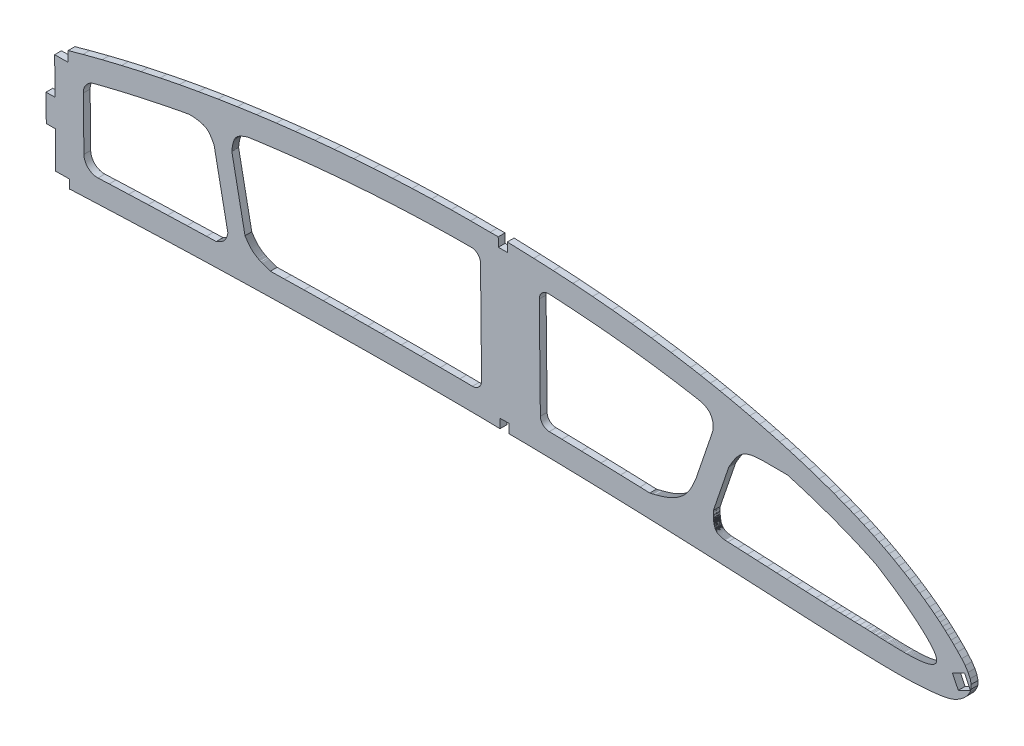
SolidWorks part; units mm, degrees
ref_plane "前视基准面" through (0, 0, 0) normal (0, 0, 1) x (1, 0, 0)
ref_plane "上视基准面" through (0, 0, 0) normal (0, 1, 0) x (1, 0, 0)
ref_plane "右视基准面" through (0, 0, 0) normal (1, 0, 0) x (0, 0, -1)
sketch "Model" plane through (0, 0, 0) normal (0, 0, 1) x (1, 0, 0)
  line L0 (245.0618, 242.5614) -> (248.3569, 243.4685)
  line L1 (248.3569, 243.4685) -> (252.624, 244.5767)
  line L2 (252.624, 244.5767) -> (256.9086, 245.6227)
  line L3 (256.9086, 245.6227) -> (261.2086, 246.6045)
  line L4 (261.2086, 246.6045) -> (265.4519, 247.5071)
  line L5 (265.4519, 247.5071) -> (269.7065, 248.3492)
  line L6 (269.7065, 248.3492) -> (273.9723, 249.1319)
  line L7 (273.9723, 249.1319) -> (278.2472, 249.8569)
  line L8 (278.2472, 249.8569) -> (282.5322, 250.5264)
  line L9 (282.5322, 250.5264) -> (286.8262, 251.1414)
  line L10 (286.8262, 251.1414) -> (291.128, 251.7046)
  line L11 (291.128, 251.7046) -> (295.4096, 252.2147)
  line L12 (295.4096, 252.2147) -> (299.696, 252.674)
  line L13 (299.696, 252.674) -> (303.9862, 253.0814)
  line L14 (303.9862, 253.0814) -> (308.2811, 253.439)
  line L15 (308.2811, 253.439) -> (312.5799, 253.7437)
  line L16 (312.5799, 253.7437) -> (316.8826, 253.9956)
  line L17 (316.8826, 253.9956) -> (321.1891, 254.1956)
  line L18 (321.1891, 254.1956) -> (325.5045, 254.341)
  line L19 (325.5045, 254.341) -> (329.8189, 254.4322)
  line L20 (329.8189, 254.4322) -> (334.1354, 254.4665)
  line L21 (334.1354, 254.4665) -> (338.45, 254.4446)
  line L22 (338.45, 254.4446) -> (340.2376, 254.4553)
  line L23 (342.2375, 254.4766) -> (348.0831, 254.2657)
  line L24 (348.0831, 254.2657) -> (352.3973, 254.0645)
  line L25 (352.3973, 254.0645) -> (356.7602, 253.7989)
  line L26 (356.7602, 253.7989) -> (361.1176, 253.4669)
  line L27 (361.1176, 253.4669) -> (365.4678, 253.0663)
  line L28 (365.4678, 253.0663) -> (369.8098, 252.5933)
  line L29 (369.8098, 252.5933) -> (374.143, 252.0446)
  line L30 (374.143, 252.0446) -> (378.4654, 251.4172)
  line L31 (378.4654, 251.4172) -> (382.7762, 250.7081)
  line L32 (382.7762, 250.7081) -> (384.9729, 250.3137)
  line L33 (384.9729, 250.3137) -> (387.1647, 249.8971)
  line L34 (387.1647, 249.8971) -> (389.3518, 249.4581)
  line L35 (389.3518, 249.4581) -> (391.5341, 248.9958)
  line L36 (391.5341, 248.9958) -> (393.7116, 248.5103)
  line L37 (393.7116, 248.5103) -> (395.8834, 248.0014)
  line L38 (395.8834, 248.0014) -> (398.0505, 247.4692)
  line L39 (398.0505, 247.4692) -> (400.2698, 246.8968)
  line L40 (400.2698, 246.8968) -> (402.4816, 246.2979)
  line L41 (402.4816, 246.2979) -> (404.6849, 245.6696)
  line L42 (404.6849, 245.6696) -> (406.8789, 245.0116)
  line L43 (406.8789, 245.0116) -> (409.0636, 244.3212)
  line L44 (409.0636, 244.3212) -> (411.2371, 243.5961)
  line L45 (411.2371, 243.5961) -> (413.4006, 242.8353)
  line L46 (413.4006, 242.8353) -> (414.5185, 242.4254)
  line L47 (414.5185, 242.4254) -> (415.6319, 242.0062)
  line L48 (415.6319, 242.0062) -> (416.7399, 241.5747)
  line L49 (416.7399, 241.5747) -> (417.8436, 241.1319)
  line L50 (417.8436, 241.1319) -> (418.9419, 240.6769)
  line L51 (418.9419, 240.6769) -> (420.0338, 240.2094)
  line L52 (420.0338, 240.2094) -> (421.1185, 239.7286)
  line L53 (421.1185, 239.7286) -> (422.2494, 239.2082)
  line L54 (422.2494, 239.2082) -> (423.3721, 238.6733)
  line L55 (423.3721, 238.6733) -> (424.4877, 238.122)
  line L56 (424.4877, 238.122) -> (425.5962, 237.5534)
  line L57 (425.5962, 237.5534) -> (426.6976, 236.9673)
  line L58 (426.6976, 236.9673) -> (427.794, 236.3629)
  line L59 (427.794, 236.3629) -> (428.8845, 235.7391)
  line L60 (428.8845, 235.7391) -> (430.0559, 235.0447)
  line L61 (430.0559, 235.0447) -> (431.2174, 234.3286)
  line L62 (431.2174, 234.3286) -> (432.3641, 233.5928)
  line L63 (432.3641, 233.5928) -> (433.4916, 232.8399)
  line L64 (433.4916, 232.8399) -> (434.596, 232.0697)
  line L65 (434.596, 232.0697) -> (435.6732, 231.2839)
  line L66 (435.6732, 231.2839) -> (436.7191, 230.4855)
  line L67 (436.7191, 230.4855) -> (437.345, 229.9878)
  line L68 (437.345, 229.9878) -> (437.9624, 229.4815)
  line L69 (437.9624, 229.4815) -> (438.5756, 228.961)
  line L70 (438.5756, 228.961) -> (439.1886, 228.4245)
  line L71 (439.1886, 228.4245) -> (439.8078, 227.8653)
  line L72 (439.8078, 227.8653) -> (440.4355, 227.2805)
  line L73 (440.4355, 227.2805) -> (441.0789, 226.6645)
  line L74 (441.0789, 226.6645) -> (441.9428, 225.8051)
  line L75 (441.9428, 225.8051) -> (442.7863, 224.8975)
  line L76 (442.7863, 224.8975) -> (443.5566, 223.9539)
  line L77 (443.5566, 223.9539) -> (444.1992, 222.9844)
  line L78 (444.1992, 222.9844) -> (444.6632, 222.0011)
  line L79 (444.6632, 222.0011) -> (444.8931, 221.0151)
  line L80 (444.8931, 221.0151) -> (444.836, 220.0386)
  line L81 (444.836, 220.0386) -> (444.6363, 219.4379)
  line L82 (444.6363, 219.4379) -> (444.3214, 218.8549)
  line L83 (444.3214, 218.8549) -> (443.908, 218.2987)
  line L84 (443.908, 218.2987) -> (443.4156, 217.7772)
  line L85 (443.4156, 217.7772) -> (442.8597, 217.2993)
  line L86 (442.8597, 217.2993) -> (442.2588, 216.8751)
  line L87 (442.2588, 216.8751) -> (441.6306, 216.5125)
  line L88 (441.6306, 216.5125) -> (441.0621, 216.2472)
  line L89 (441.0621, 216.2472) -> (440.486, 216.0306)
  line L90 (440.486, 216.0306) -> (439.9046, 215.8568)
  line L91 (439.9046, 215.8568) -> (439.3184, 215.7168)
  line L92 (439.3184, 215.7168) -> (438.7276, 215.6046)
  line L93 (438.7276, 215.6046) -> (438.1337, 215.5132)
  line L94 (438.1337, 215.5132) -> (437.537, 215.4347)
  line L95 (437.537, 215.4347) -> (436.4701, 215.3127)
  line L96 (436.4701, 215.3127) -> (435.4002, 215.2084)
  line L97 (435.4002, 215.2084) -> (434.3262, 215.123)
  line L98 (434.3262, 215.123) -> (433.2504, 215.0536)
  line L99 (433.2504, 215.0536) -> (432.1727, 215)
  line L100 (432.1727, 215) -> (431.0943, 214.9604)
  line L101 (431.0943, 214.9604) -> (430.0151, 214.9348)
  line L102 (430.0151, 214.9348) -> (428.9342, 214.9211)
  line L103 (428.9342, 214.9211) -> (427.8547, 214.9196)
  line L104 (427.8547, 214.9196) -> (426.7758, 214.926)
  line L105 (426.7758, 214.926) -> (425.6974, 214.9415)
  line L106 (425.6974, 214.9415) -> (424.6187, 214.962)
  line L107 (424.6187, 214.962) -> (423.5407, 214.9876)
  line L108 (423.5407, 214.9876) -> (422.4615, 215.016)
  line L109 (422.4615, 215.016) -> (421.3814, 215.0455)
  line L110 (421.3814, 215.0455) -> (420.3011, 215.0769)
  line L111 (420.3011, 215.0769) -> (419.2207, 215.1103)
  line L112 (419.2207, 215.1103) -> (418.1402, 215.1447)
  line L113 (418.1402, 215.1447) -> (417.0596, 215.1812)
  line L114 (417.0596, 215.1812) -> (415.9799, 215.2196)
  line L115 (415.9799, 215.2196) -> (414.8992, 215.26)
  line L116 (414.8992, 215.26) -> (412.7353, 215.3467)
  line L117 (412.7353, 215.3467) -> (410.573, 215.4405)
  line L118 (410.573, 215.4405) -> (408.4104, 215.5403)
  line L119 (408.4104, 215.5403) -> (406.2485, 215.6452)
  line L120 (406.2485, 215.6452) -> (404.0865, 215.752)
  line L121 (404.0865, 215.752) -> (401.9254, 215.8609)
  line L122 (401.9254, 215.8609) -> (399.7623, 215.9707)
  line L123 (399.7623, 215.9707) -> (397.5993, 216.0785)
  line L124 (397.5993, 216.0785) -> (395.4373, 216.1853)
  line L125 (395.4373, 216.1853) -> (393.2754, 216.2901)
  line L126 (393.2754, 216.2901) -> (391.1136, 216.394)
  line L127 (391.1136, 216.394) -> (388.9509, 216.4948)
  line L128 (388.9509, 216.4948) -> (386.7884, 216.5936)
  line L129 (386.7884, 216.5936) -> (384.625, 216.6893)
  line L130 (384.625, 216.6893) -> (380.3037, 216.8731)
  line L131 (380.3037, 216.8731) -> (375.983, 217.0439)
  line L132 (375.983, 217.0439) -> (371.662, 217.2036)
  line L133 (371.662, 217.2036) -> (367.3417, 217.3504)
  line L134 (367.3417, 217.3504) -> (363.02, 217.4841)
  line L135 (363.02, 217.4841) -> (358.6972, 217.6037)
  line L136 (358.6972, 217.6037) -> (354.373, 217.7102)
  line L137 (354.373, 217.7102) -> (350.0557, 217.802)
  line L138 (350.0557, 217.802) -> (346.1306, 217.8729)
  line L139 (340.6274, 217.8782) -> (336.1058, 217.9526)
  line L140 (336.1058, 217.9526) -> (331.7905, 217.9885)
  line L141 (331.7905, 217.9885) -> (327.4729, 218.0102)
  line L142 (327.4729, 218.0102) -> (323.1551, 218.0179)
  line L143 (323.1551, 218.0179) -> (318.8421, 218.0119)
  line L144 (318.8421, 218.0119) -> (314.5309, 217.9919)
  line L145 (314.5309, 217.9919) -> (310.2202, 217.9599)
  line L146 (310.2202, 217.9599) -> (305.9093, 217.9149)
  line L147 (305.9093, 217.9149) -> (301.5991, 217.858)
  line L148 (301.5991, 217.858) -> (297.2874, 217.7899)
  line L149 (297.2874, 217.7899) -> (292.9753, 217.7108)
  line L150 (292.9753, 217.7108) -> (288.6659, 217.6208)
  line L151 (288.6659, 217.6208) -> (284.358, 217.5209)
  line L152 (284.358, 217.5209) -> (280.0516, 217.411)
  line L153 (280.0516, 217.411) -> (275.7447, 217.2911)
  line L154 (275.7447, 217.2911) -> (271.4384, 217.1613)
  line L155 (271.4384, 217.1613) -> (267.1317, 217.0214)
  line L156 (267.1317, 217.0214) -> (262.8244, 216.8734)
  line L157 (262.8244, 216.8734) -> (258.5186, 216.7155)
  line L158 (258.5186, 216.7155) -> (254.2142, 216.5497)
  line L159 (254.2142, 216.5497) -> (249.9103, 216.3769)
  line L160 (249.9103, 216.3769) -> (245.6076, 216.1981)
  line L161 (245.6076, 216.1981) -> (245.3439, 216.09)
  line L162 (421.8638, 220.0305) -> (421.3281, 220.0452)
  line L163 (421.3281, 220.0452) -> (420.2478, 220.0766)
  line L164 (420.2478, 220.0766) -> (419.1674, 220.11)
  line L165 (419.1674, 220.11) -> (418.0869, 220.1445)
  line L166 (418.0869, 220.1445) -> (417.0063, 220.1809)
  line L167 (417.0063, 220.1809) -> (415.9267, 220.2193)
  line L168 (415.9267, 220.2193) -> (414.8459, 220.2598)
  line L169 (414.8459, 220.2598) -> (413.7639, 220.3031)
  line L170 (412.3001, 220.363) -> (410.5197, 220.4403)
  line L171 (410.5197, 220.4403) -> (408.3571, 220.54)
  line L172 (408.3571, 220.54) -> (406.1952, 220.6449)
  line L173 (406.1952, 220.6449) -> (404.0332, 220.7517)
  line L174 (404.0332, 220.7517) -> (401.8721, 220.8606)
  line L175 (401.8721, 220.8606) -> (399.709, 220.9704)
  line L176 (399.709, 220.9704) -> (397.546, 221.0782)
  line L177 (397.546, 221.0782) -> (395.384, 221.185)
  line L178 (395.384, 221.185) -> (393.2221, 221.2899)
  line L179 (393.2221, 221.2899) -> (391.0603, 221.3937)
  line L180 (391.0603, 221.3937) -> (390.3821, 221.4253)
  line L181 (373.7692, 222.1235) -> (371.6087, 222.2033)
  line L182 (371.6087, 222.2033) -> (367.2884, 222.3501)
  line L183 (367.2884, 222.3501) -> (362.9667, 222.4838)
  line L184 (362.9667, 222.4838) -> (358.6439, 222.6034)
  line L185 (358.6439, 222.6034) -> (354.3197, 222.7099)
  line L186 (354.3197, 222.7099) -> (351.5149, 222.7696)
  line L187 (349.5575, 224.7478) -> (349.3193, 247.0941)
  line L188 (351.4124, 249.1132) -> (352.4506, 249.0648)
  line L189 (352.4506, 249.0648) -> (356.8135, 248.7992)
  line L190 (356.8135, 248.7992) -> (361.1709, 248.4672)
  line L191 (361.1709, 248.4672) -> (365.5211, 248.0666)
  line L192 (365.5211, 248.0666) -> (369.8631, 247.5936)
  line L193 (373.6956, 247.1083) -> (374.1963, 247.0449)
  line L194 (374.1963, 247.0449) -> (378.5187, 246.4175)
  line L195 (378.5187, 246.4175) -> (382.8295, 245.7084)
  line L196 (382.8295, 245.7084) -> (385.0223, 245.3142)
  line L197 (404.2541, 240.8079) -> (404.7382, 240.6698)
  line L198 (404.7382, 240.6698) -> (406.9322, 240.0119)
  line L199 (406.9322, 240.0119) -> (409.1168, 239.3215)
  line L200 (409.1168, 239.3215) -> (411.2904, 238.5963)
  line L201 (411.2904, 238.5963) -> (413.4539, 237.8356)
  line L202 (413.4539, 237.8356) -> (414.5718, 237.4257)
  line L203 (414.5718, 237.4257) -> (415.6851, 237.0065)
  line L204 (415.6851, 237.0065) -> (416.7932, 236.575)
  line L205 (416.7932, 236.575) -> (417.8968, 236.1322)
  line L206 (417.8968, 236.1322) -> (418.9952, 235.6771)
  line L207 (418.9952, 235.6771) -> (420.0871, 235.2097)
  line L208 (420.0871, 235.2097) -> (421.1718, 234.7289)
  line L209 (421.1718, 234.7289) -> (422.3027, 234.2085)
  line L210 (422.3027, 234.2085) -> (423.4254, 233.6736)
  line L211 (423.4254, 233.6736) -> (423.9815, 233.3978)
  line L212 (334.5349, 222.965) -> (331.7372, 222.9882)
  line L213 (331.7372, 222.9882) -> (327.4196, 223.01)
  line L214 (327.4196, 223.01) -> (323.1019, 223.0177)
  line L215 (323.1019, 223.0177) -> (318.7888, 223.0116)
  line L216 (318.7888, 223.0116) -> (314.4776, 222.9916)
  line L217 (314.4776, 222.9916) -> (311.3864, 222.9687)
  line L218 (308.0115, 222.9372) -> (305.856, 222.9147)
  line L219 (305.856, 222.9147) -> (301.5458, 222.8577)
  line L220 (301.5458, 222.8577) -> (297.2341, 222.7896)
  line L221 (297.2341, 222.7896) -> (292.9221, 222.7105)
  line L222 (292.9221, 222.7105) -> (289.7999, 222.6451)
  line L223 (277.8427, 222.3507) -> (275.6914, 222.2909)
  line L224 (275.6914, 222.2909) -> (271.3851, 222.161)
  line L225 (271.3851, 222.161) -> (267.0784, 222.0211)
  line L226 (267.0784, 222.0211) -> (262.7711, 221.8731)
  line L227 (262.7711, 221.8731) -> (258.4653, 221.7152)
  line L228 (258.4653, 221.7152) -> (254.161, 221.5494)
  line L229 (254.161, 221.5494) -> (251.6801, 221.4498)
  line L230 (248.5599, 224.4154) -> (248.4352, 236.1229)
  line L231 (250.6809, 239.0585) -> (252.6773, 239.577)
  line L232 (252.6773, 239.577) -> (256.9619, 240.623)
  line L233 (256.9619, 240.623) -> (259.1119, 241.1139)
  line L234 (262.097, 241.7824) -> (265.5052, 242.5074)
  line L235 (265.5052, 242.5074) -> (269.7598, 243.3495)
  line L236 (269.7598, 243.3495) -> (271.894, 243.7404)
  line L237 (284.7324, 245.8344) -> (286.8795, 246.1416)
  line L238 (286.8795, 246.1416) -> (291.1812, 246.7049)
  line L239 (291.1812, 246.7049) -> (295.4629, 247.215)
  line L240 (295.4629, 247.215) -> (299.7493, 247.6743)
  line L241 (299.7493, 247.6743) -> (304.0395, 248.0817)
  line L242 (304.0395, 248.0817) -> (308.3344, 248.4393)
  line L243 (308.3344, 248.4393) -> (312.6332, 248.744)
  line L244 (312.6332, 248.744) -> (316.9359, 248.9959)
  line L245 (316.9359, 248.9959) -> (321.2424, 249.1958)
  line L246 (321.2424, 249.1958) -> (325.5578, 249.3412)
  line L247 (325.5578, 249.3412) -> (329.8722, 249.4325)
  line L248 (329.8722, 249.4325) -> (334.1887, 249.4668)
  line L249 (334.1887, 249.4668) -> (334.3219, 249.4661)
  line L250 (336.3116, 247.4874) -> (336.5515, 224.9862)
  line L251 (444.7279, 219.7736) -> (443.4043, 222.4658)
  line L252 (443.4043, 222.4658) -> (440.7121, 221.1422)
  line L253 (440.7121, 221.1422) -> (442.0357, 218.45)
  line L254 (442.0357, 218.45) -> (444.7279, 219.7736)
  line L255 (242.0859, 240.2764) -> (245.0858, 240.3084)
  line L256 (245.0858, 240.3084) -> (245.0618, 242.5614)
  line L257 (245.3439, 216.09) -> (245.3226, 218.0899)
  line L258 (245.3226, 218.0899) -> (242.3228, 218.0579)
  line L259 (242.0859, 240.2764) -> (242.1724, 232.1669)
  line L260 (242.1724, 232.1669) -> (240.1725, 232.1456)
  line L261 (240.1725, 232.1456) -> (240.2364, 226.1459)
  line L262 (240.2364, 226.1459) -> (242.2363, 226.1672)
  line L263 (242.2363, 226.1672) -> (242.3228, 218.0579)
  line L264 (346.1306, 217.8729) -> (343.6273, 217.8919)
  line L265 (340.2589, 252.4554) -> (342.2588, 252.4767)
  line L266 (342.606, 219.8994) -> (340.6061, 219.8781)
  line L267 (340.2589, 252.4554) -> (340.2376, 254.4553)
  line L268 (342.2588, 252.4767) -> (342.2375, 254.4766)
  line L269 (340.6061, 219.8781) -> (340.6274, 217.8782)
  line L270 (342.606, 219.8994) -> (342.6273, 217.8995)
  line L271 (369.8631, 247.5936) -> (373.6956, 247.1083)
  line L272 (343.6273, 217.8919) -> (342.6273, 217.8995)
  line L273 (259.1119, 241.1139) -> (262.097, 241.7824)
  line L274 (308.0115, 222.9372) -> (311.3864, 222.9687)
  line L275 (412.3001, 220.363) -> (413.7639, 220.3031)
  line L276 (280.4111, 225.2921) -> (277.3782, 240.5637)
  line L277 (281.2901, 241.3404) -> (284.2069, 226.6477)
  line L278 (387.8402, 225.8192) -> (391.2439, 235.813)
  line L279 (384.0049, 230.0495) -> (387.68, 240.8503)
  line L280 (423.9815, 233.3978) -> (424.1224, 233.3123)
  line L281 (424.1224, 233.3123) -> (424.2533, 233.2267)
  line L282 (424.2533, 233.2267) -> (424.3843, 233.1411)
  line L283 (424.3843, 233.1411) -> (424.5252, 233.0546)
  line L284 (424.5252, 233.0546) -> (424.6561, 232.969)
  line L285 (424.6561, 232.969) -> (424.787, 232.8834)
  line L286 (424.787, 232.8834) -> (424.928, 232.7969)
  line L287 (424.928, 232.7969) -> (425.0589, 232.7103)
  line L288 (425.0589, 232.7103) -> (425.1998, 232.6237)
  line L289 (425.1998, 232.6237) -> (425.3307, 232.5371)
  line L290 (425.3307, 232.5371) -> (425.4617, 232.4505)
  line L291 (425.4617, 232.4505) -> (425.6026, 232.363)
  line L292 (425.6026, 232.363) -> (425.7336, 232.2754)
  line L293 (425.7336, 232.2754) -> (425.8745, 232.1879)
  line L294 (425.8745, 232.1879) -> (426.0054, 232.0993)
  line L295 (426.0054, 232.0993) -> (426.1464, 232.0108)
  line L296 (426.1464, 232.0108) -> (426.2774, 231.9222)
  line L297 (426.2774, 231.9222) -> (426.4183, 231.8337)
  line L298 (426.4183, 231.8337) -> (426.5493, 231.7431)
  line L299 (426.5493, 231.7431) -> (426.6902, 231.6536)
  line L300 (426.6902, 231.6536) -> (426.8212, 231.563)
  line L301 (426.8212, 231.563) -> (426.9622, 231.4715)
  line L302 (426.9622, 231.4715) -> (427.1032, 231.38)
  line L303 (427.1032, 231.38) -> (427.2342, 231.2884)
  line L304 (427.2342, 231.2884) -> (427.3752, 231.1959)
  line L305 (427.3752, 231.1959) -> (427.5162, 231.1023)
  line L306 (427.5162, 231.1023) -> (427.6472, 231.0087)
  line L307 (427.6472, 231.0087) -> (427.7882, 230.9142)
  line L308 (427.7882, 230.9142) -> (427.9292, 230.8187)
  line L309 (427.9292, 230.8187) -> (428.0702, 230.7232)
  line L310 (428.0702, 230.7232) -> (428.2113, 230.6267)
  line L311 (428.2113, 230.6267) -> (428.3523, 230.5302)
  line L312 (428.3523, 230.5302) -> (428.4934, 230.4317)
  line L313 (428.4934, 230.4317) -> (428.6244, 230.3331)
  line L314 (428.6244, 230.3331) -> (428.7655, 230.2336)
  line L315 (428.7655, 230.2336) -> (428.9166, 230.1332)
  line L316 (428.9166, 230.1332) -> (429.0576, 230.0327)
  line L317 (429.0576, 230.0327) -> (429.1987, 229.9302)
  line L318 (429.1987, 229.9302) -> (429.3398, 229.8277)
  line L319 (429.3398, 229.8277) -> (429.481, 229.7242)
  line L320 (429.481, 229.7242) -> (429.6221, 229.6197)
  line L321 (429.6221, 229.6197) -> (429.7732, 229.5133)
  line L322 (429.7732, 229.5133) -> (429.9144, 229.4068)
  line L323 (429.9144, 229.4068) -> (430.0555, 229.2993)
  line L324 (430.0555, 229.2993) -> (430.2067, 229.1909)
  line L325 (430.2067, 229.1909) -> (430.3479, 229.0814)
  line L326 (430.3479, 229.0814) -> (430.499, 228.971)
  line L327 (430.499, 228.971) -> (430.6403, 228.8585)
  line L328 (430.6403, 228.8585) -> (430.7915, 228.7461)
  line L329 (430.7915, 228.7461) -> (430.9427, 228.6317)
  line L330 (430.9427, 228.6317) -> (431.0939, 228.5173)
  line L331 (431.0939, 228.5173) -> (431.2352, 228.4008)
  line L332 (431.2352, 228.4008) -> (431.3864, 228.2824)
  line L333 (431.3864, 228.2824) -> (431.5377, 228.164)
  line L334 (431.5377, 228.164) -> (431.689, 228.0437)
  line L335 (431.689, 228.0437) -> (431.8403, 227.9233)
  line L336 (431.8403, 227.9233) -> (431.9916, 227.7999)
  line L337 (431.9916, 227.7999) -> (432.1429, 227.6765)
  line L338 (432.1429, 227.6765) -> (432.3043, 227.5512)
  line L339 (432.3043, 227.5512) -> (432.4556, 227.4248)
  line L340 (432.4556, 227.4248) -> (432.607, 227.2964)
  line L341 (432.607, 227.2964) -> (432.7684, 227.1681)
  line L342 (432.7684, 227.1681) -> (432.9198, 227.0377)
  line L343 (432.9198, 227.0377) -> (433.0712, 226.9063)
  line L344 (433.0712, 226.9063) -> (433.2326, 226.775)
  line L345 (433.2326, 226.775) -> (433.384, 226.6416)
  line L346 (433.384, 226.6416) -> (433.5355, 226.5082)
  line L347 (433.5355, 226.5082) -> (433.6869, 226.3739)
  line L348 (433.6869, 226.3739) -> (433.8383, 226.2395)
  line L349 (433.8383, 226.2395) -> (433.9898, 226.1051)
  line L350 (433.9898, 226.1051) -> (434.1412, 225.9697)
  line L351 (434.1412, 225.9697) -> (434.2927, 225.8343)
  line L352 (434.2927, 225.8343) -> (434.4341, 225.6988)
  line L353 (434.4341, 225.6988) -> (434.5856, 225.5624)
  line L354 (434.5856, 225.5624) -> (434.7271, 225.4269)
  line L355 (434.7271, 225.4269) -> (434.8685, 225.2914)
  line L356 (434.8685, 225.2914) -> (435.01, 225.1559)
  line L357 (435.01, 225.1559) -> (435.1414, 225.0213)
  line L358 (435.1414, 225.0213) -> (435.2728, 224.8867)
  line L359 (435.2728, 224.8867) -> (435.4043, 224.7521)
  line L360 (435.4043, 224.7521) -> (435.5357, 224.6195)
  line L361 (435.5357, 224.6195) -> (435.6571, 224.4857)
  line L362 (435.6571, 224.4857) -> (435.7786, 224.354)
  line L363 (435.7786, 224.354) -> (435.9, 224.2233)
  line L364 (435.9, 224.2233) -> (436.0114, 224.0925)
  line L365 (436.0114, 224.0925) -> (436.1227, 223.9637)
  line L366 (436.1227, 223.9637) -> (436.2241, 223.8357)
  line L367 (436.2241, 223.8357) -> (436.3255, 223.7088)
  line L368 (436.3255, 223.7088) -> (436.4268, 223.5839)
  line L369 (436.4268, 223.5839) -> (436.5181, 223.4599)
  line L370 (436.5181, 223.4599) -> (436.6094, 223.3368)
  line L371 (436.6094, 223.3368) -> (436.6907, 223.2167)
  line L372 (436.6907, 223.2167) -> (436.772, 223.0975)
  line L373 (436.772, 223.0975) -> (436.8433, 222.9803)
  line L374 (436.8433, 222.9803) -> (436.9145, 222.8651)
  line L375 (436.9145, 222.8651) -> (436.9757, 222.7517)
  line L376 (436.9757, 222.7517) -> (437.0269, 222.6402)
  line L377 (437.0269, 222.6402) -> (437.0781, 222.5308)
  line L378 (437.0781, 222.5308) -> (437.1292, 222.4233)
  line L379 (437.1292, 222.4233) -> (437.1603, 222.3196)
  line L380 (437.1603, 222.3196) -> (437.1914, 222.217)
  line L381 (437.1914, 222.217) -> (437.2225, 222.1173)
  line L382 (437.2225, 222.1173) -> (437.2435, 222.0205)
  line L383 (437.2435, 222.0205) -> (437.2545, 221.9256)
  line L384 (437.2545, 221.9256) -> (437.2555, 221.8336)
  line L385 (437.2555, 221.8336) -> (437.2565, 221.7436)
  line L386 (437.2565, 221.7436) -> (437.2474, 221.6565)
  line L387 (437.2474, 221.6565) -> (437.2383, 221.5714)
  line L388 (437.2383, 221.5714) -> (437.2192, 221.4892)
  line L389 (437.2192, 221.4892) -> (437.19, 221.4089)
  line L390 (437.19, 221.4089) -> (437.1608, 221.3316)
  line L391 (437.1608, 221.3316) -> (437.1217, 221.2552)
  line L392 (437.1217, 221.2552) -> (437.0824, 221.1827)
  line L393 (437.0824, 221.1827) -> (437.0332, 221.1112)
  line L394 (437.0332, 221.1112) -> (436.9839, 221.0417)
  line L395 (436.9839, 221.0417) -> (436.9146, 220.9749)
  line L396 (436.9146, 220.9749) -> (436.8553, 220.9103)
  line L397 (436.8553, 220.9103) -> (436.786, 220.8476)
  line L398 (436.786, 220.8476) -> (436.7066, 220.7877)
  line L399 (436.7066, 220.7877) -> (436.6272, 220.7289)
  line L400 (436.6272, 220.7289) -> (436.5378, 220.6719)
  line L401 (436.5378, 220.6719) -> (436.4484, 220.618)
  line L402 (436.4484, 220.618) -> (436.349, 220.5649)
  line L403 (436.349, 220.5649) -> (436.2495, 220.5148)
  line L404 (436.2495, 220.5148) -> (436.14, 220.4657)
  line L405 (436.14, 220.4657) -> (436.0305, 220.4195)
  line L406 (436.0305, 220.4195) -> (435.911, 220.3742)
  line L407 (435.911, 220.3742) -> (435.7914, 220.3309)
  line L408 (435.7914, 220.3309) -> (435.6619, 220.2896)
  line L409 (435.6619, 220.2896) -> (435.5323, 220.2502)
  line L410 (435.5323, 220.2502) -> (435.4027, 220.2118)
  line L411 (435.4027, 220.2118) -> (435.2631, 220.1753)
  line L412 (435.2631, 220.1753) -> (435.1134, 220.1407)
  line L413 (435.1134, 220.1407) -> (434.9738, 220.1082)
  line L414 (434.9738, 220.1082) -> (434.8141, 220.0775)
  line L415 (434.8141, 220.0775) -> (434.6644, 220.0469)
  line L416 (434.6644, 220.0469) -> (434.5047, 220.0192)
  line L417 (434.5047, 220.0192) -> (434.335, 219.9924)
  line L418 (434.335, 219.9924) -> (434.1652, 219.9676)
  line L419 (434.1652, 219.9676) -> (433.9955, 219.9438)
  line L420 (433.9955, 219.9438) -> (433.8157, 219.9219)
  line L421 (433.8157, 219.9219) -> (433.6359, 219.9009)
  line L422 (433.6359, 219.9009) -> (433.4561, 219.882)
  line L423 (433.4561, 219.882) -> (433.2663, 219.864)
  line L424 (433.2663, 219.864) -> (433.0764, 219.847)
  line L425 (433.0764, 219.847) -> (432.8866, 219.8319)
  line L426 (432.8866, 219.8319) -> (432.6867, 219.8178)
  line L427 (432.6867, 219.8178) -> (432.4869, 219.8047)
  line L428 (432.4869, 219.8047) -> (432.287, 219.7926)
  line L429 (432.287, 219.7926) -> (432.0771, 219.7823)
  line L430 (432.0771, 219.7823) -> (431.8672, 219.7731)
  line L431 (431.8672, 219.7731) -> (431.6572, 219.7648)
  line L432 (431.6572, 219.7648) -> (431.4473, 219.7586)
  line L433 (431.4473, 219.7586) -> (431.2273, 219.7523)
  line L434 (431.2273, 219.7523) -> (431.0074, 219.7469)
  line L435 (431.0074, 219.7469) -> (430.7774, 219.7435)
  line L436 (430.7774, 219.7435) -> (430.5574, 219.7401)
  line L437 (430.5574, 219.7401) -> (430.3274, 219.7387)
  line L438 (430.3274, 219.7387) -> (430.0974, 219.7372)
  line L439 (430.0974, 219.7372) -> (429.8674, 219.7378)
  line L440 (429.8674, 219.7378) -> (429.6274, 219.7382)
  line L441 (429.6274, 219.7382) -> (429.3874, 219.7396)
  line L442 (429.3874, 219.7396) -> (429.1473, 219.7421)
  line L443 (429.1473, 219.7421) -> (428.9073, 219.7455)
  line L444 (428.9073, 219.7455) -> (428.6672, 219.75)
  line L445 (428.6672, 219.75) -> (428.4172, 219.7543)
  line L446 (428.4172, 219.7543) -> (428.1671, 219.7596)
  line L447 (428.1671, 219.7596) -> (427.927, 219.7661)
  line L448 (427.927, 219.7661) -> (427.6669, 219.7733)
  line L449 (427.6669, 219.7733) -> (427.4168, 219.7806)
  line L450 (427.4168, 219.7806) -> (427.1667, 219.789)
  line L451 (427.1667, 219.789) -> (426.9066, 219.7972)
  line L452 (426.9066, 219.7972) -> (426.6565, 219.8065)
  line L453 (426.6565, 219.8065) -> (426.3964, 219.8158)
  line L454 (426.3964, 219.8158) -> (426.1363, 219.826)
  line L455 (426.1363, 219.826) -> (425.8761, 219.8362)
  line L456 (425.8761, 219.8362) -> (425.606, 219.8474)
  line L457 (425.606, 219.8474) -> (425.3459, 219.8586)
  line L458 (425.3459, 219.8586) -> (425.0857, 219.8708)
  line L459 (425.0857, 219.8708) -> (424.8156, 219.8829)
  line L460 (424.8156, 219.8829) -> (424.5554, 219.8952)
  line L461 (424.5554, 219.8952) -> (424.2853, 219.9083)
  line L462 (424.2853, 219.9083) -> (424.0151, 219.9214)
  line L463 (424.0151, 219.9214) -> (423.755, 219.9346)
  line L464 (423.755, 219.9346) -> (423.4848, 219.9477)
  line L465 (423.4848, 219.9477) -> (423.2147, 219.9609)
  line L466 (423.2147, 219.9609) -> (422.9445, 219.975)
  line L467 (422.9445, 219.975) -> (422.6743, 219.9881)
  line L468 (422.6743, 219.9881) -> (422.4042, 220.0022)
  line L469 (422.4042, 220.0022) -> (422.134, 220.0164)
  line L470 (422.134, 220.0164) -> (421.8638, 220.0305)
  line L471 (404.2541, 240.8079) -> (404.1814, 240.8082)
  line L472 (404.1814, 240.8082) -> (404.1014, 240.8093)
  line L473 (404.1014, 240.8093) -> (404.0214, 240.8095)
  line L474 (404.0214, 240.8095) -> (403.9413, 240.8106)
  line L475 (403.9413, 240.8106) -> (403.8713, 240.8109)
  line L476 (403.8713, 240.8109) -> (403.7913, 240.812)
  line L477 (403.7913, 240.812) -> (403.7113, 240.8122)
  line L478 (403.7113, 240.8122) -> (403.6313, 240.8133)
  line L479 (403.6313, 240.8133) -> (403.5513, 240.8135)
  line L480 (403.5513, 240.8135) -> (403.4813, 240.8137)
  line L481 (403.4813, 240.8137) -> (403.4013, 240.8149)
  line L482 (403.4013, 240.8149) -> (403.3213, 240.815)
  line L483 (403.3213, 240.815) -> (403.2412, 240.8162)
  line L484 (403.2412, 240.8162) -> (403.1712, 240.8164)
  line L485 (403.1712, 240.8164) -> (403.0912, 240.8176)
  line L486 (403.0912, 240.8176) -> (403.0112, 240.8177)
  line L487 (403.0112, 240.8177) -> (402.9312, 240.8179)
  line L488 (402.9312, 240.8179) -> (402.8512, 240.819)
  line L489 (402.8512, 240.819) -> (402.7812, 240.8193)
  line L490 (402.7812, 240.8193) -> (402.7012, 240.8194)
  line L491 (402.7012, 240.8194) -> (402.6212, 240.8206)
  line L492 (402.6212, 240.8206) -> (402.5412, 240.8207)
  line L493 (402.5412, 240.8207) -> (402.4611, 240.8219)
  line L494 (402.4611, 240.8219) -> (402.3911, 240.8221)
  line L495 (402.3911, 240.8221) -> (402.3111, 240.8223)
  line L496 (402.3111, 240.8223) -> (402.2311, 240.8224)
  line L497 (402.2311, 240.8224) -> (402.1511, 240.8236)
  line L498 (402.1511, 240.8236) -> (402.0711, 240.8237)
  line L499 (402.0711, 240.8237) -> (401.9911, 240.8238)
  line L500 (401.9911, 240.8238) -> (401.9211, 240.8251)
  line L501 (401.9211, 240.8251) -> (401.8411, 240.8253)
  line L502 (401.8411, 240.8253) -> (401.7611, 240.8254)
  line L503 (401.7611, 240.8254) -> (401.6811, 240.8255)
  line L504 (401.6811, 240.8255) -> (401.6011, 240.8257)
  line L505 (401.6011, 240.8257) -> (401.521, 240.8268)
  line L506 (401.521, 240.8268) -> (401.441, 240.827)
  line L507 (401.441, 240.827) -> (401.361, 240.8271)
  line L508 (401.361, 240.8271) -> (401.281, 240.8273)
  line L509 (401.281, 240.8273) -> (401.201, 240.8274)
  line L510 (401.201, 240.8274) -> (401.121, 240.8276)
  line L511 (401.121, 240.8276) -> (401.041, 240.8277)
  line L512 (401.041, 240.8277) -> (400.971, 240.828)
  line L513 (400.971, 240.828) -> (400.891, 240.8281)
  line L514 (400.891, 240.8281) -> (400.811, 240.8283)
  line L515 (400.811, 240.8283) -> (400.731, 240.8284)
  line L516 (400.731, 240.8284) -> (400.641, 240.8285)
  line L517 (400.641, 240.8285) -> (400.561, 240.8286)
  line L518 (400.561, 240.8286) -> (400.481, 240.8288)
  line L519 (400.481, 240.8288) -> (400.401, 240.8289)
  line L520 (400.401, 240.8289) -> (400.3209, 240.829)
  line L521 (400.3209, 240.829) -> (400.2409, 240.8292)
  line L522 (400.2409, 240.8292) -> (400.1609, 240.8293)
  line L523 (400.1609, 240.8293) -> (400.0809, 240.8295)
  line L524 (400.0809, 240.8295) -> (400.0009, 240.8286)
  line L525 (400.0009, 240.8286) -> (399.9209, 240.8288)
  line L526 (399.9209, 240.8288) -> (399.8409, 240.8289)
  line L527 (399.8409, 240.8289) -> (399.7509, 240.829)
  line L528 (399.7509, 240.829) -> (399.6709, 240.8281)
  line L529 (399.6709, 240.8281) -> (399.5909, 240.8283)
  line L530 (399.5909, 240.8283) -> (399.5109, 240.8274)
  line L531 (399.5109, 240.8274) -> (399.4309, 240.8276)
  line L532 (399.4309, 240.8276) -> (399.3409, 240.8276)
  line L533 (399.3409, 240.8276) -> (399.2609, 240.8268)
  line L534 (399.2609, 240.8268) -> (399.1809, 240.8259)
  line L535 (399.1809, 240.8259) -> (399.1009, 240.826)
  line L536 (399.1009, 240.826) -> (399.0109, 240.8251)
  line L537 (399.0109, 240.8251) -> (398.9309, 240.8242)
  line L538 (398.9309, 240.8242) -> (398.8509, 240.8224)
  line L539 (398.8509, 240.8224) -> (398.7609, 240.8214)
  line L540 (398.7609, 240.8214) -> (398.681, 240.8196)
  line L541 (398.681, 240.8196) -> (398.601, 240.8187)
  line L542 (398.601, 240.8187) -> (398.521, 240.8169)
  line L543 (398.521, 240.8169) -> (398.431, 240.8139)
  line L544 (398.431, 240.8139) -> (398.351, 240.8121)
  line L545 (398.351, 240.8121) -> (398.271, 240.8092)
  line L546 (398.271, 240.8092) -> (398.1811, 240.8062)
  line L547 (398.1811, 240.8062) -> (398.1011, 240.8024)
  line L548 (398.1011, 240.8024) -> (398.0211, 240.7995)
  line L549 (398.0211, 240.7995) -> (397.9412, 240.7947)
  line L550 (397.9412, 240.7947) -> (397.8512, 240.7907)
  line L551 (397.8512, 240.7907) -> (397.7713, 240.7859)
  line L552 (397.7713, 240.7859) -> (397.6913, 240.781)
  line L553 (397.6913, 240.781) -> (397.6114, 240.7752)
  line L554 (397.6114, 240.7752) -> (397.5314, 240.7693)
  line L555 (397.5314, 240.7693) -> (397.4415, 240.7624)
  line L556 (397.4415, 240.7624) -> (397.3616, 240.7555)
  line L557 (397.3616, 240.7555) -> (397.2816, 240.7487)
  line L558 (397.2816, 240.7487) -> (397.2017, 240.7398)
  line L559 (397.2017, 240.7398) -> (397.1218, 240.7319)
  line L560 (397.1218, 240.7319) -> (397.0419, 240.7231)
  line L561 (397.0419, 240.7231) -> (396.962, 240.7132)
  line L562 (396.962, 240.7132) -> (396.8821, 240.7034)
  line L563 (396.8821, 240.7034) -> (396.8022, 240.6925)
  line L564 (396.8022, 240.6925) -> (396.7223, 240.6807)
  line L565 (396.7223, 240.6807) -> (396.6424, 240.6688)
  line L566 (396.6424, 240.6688) -> (396.5626, 240.656)
  line L567 (396.5626, 240.656) -> (396.4827, 240.6431)
  line L568 (396.4827, 240.6431) -> (396.4029, 240.6293)
  line L569 (396.4029, 240.6293) -> (396.333, 240.6145)
  line L570 (396.333, 240.6145) -> (396.2532, 240.5997)
  line L571 (396.2532, 240.5997) -> (396.1733, 240.5828)
  line L572 (396.1733, 240.5828) -> (396.0935, 240.567)
  line L573 (396.0935, 240.567) -> (396.0237, 240.5492)
  line L574 (396.0237, 240.5492) -> (395.9439, 240.5304)
  line L575 (395.9439, 240.5304) -> (395.8741, 240.5116)
  line L576 (395.8741, 240.5116) -> (395.7943, 240.4918)
  line L577 (395.7943, 240.4918) -> (395.7245, 240.471)
  line L578 (395.7245, 240.471) -> (395.6447, 240.4492)
  line L579 (395.6447, 240.4492) -> (395.575, 240.4264)
  line L580 (395.575, 240.4264) -> (395.5052, 240.4037)
  line L581 (395.5052, 240.4037) -> (395.4255, 240.3788)
  line L582 (395.4255, 240.3788) -> (395.3557, 240.3541)
  line L583 (395.3557, 240.3541) -> (395.286, 240.3284)
  line L584 (395.286, 240.3284) -> (395.2163, 240.3006)
  line L585 (395.2163, 240.3006) -> (395.1466, 240.2729)
  line L586 (395.1466, 240.2729) -> (395.0769, 240.2441)
  line L587 (395.0769, 240.2441) -> (395.0072, 240.2144)
  line L588 (395.0072, 240.2144) -> (394.9375, 240.1836)
  line L589 (394.9375, 240.1836) -> (394.8679, 240.1509)
  line L590 (394.8679, 240.1509) -> (394.7982, 240.1181)
  line L591 (394.7982, 240.1181) -> (394.7386, 240.0835)
  line L592 (394.7386, 240.0835) -> (394.6689, 240.0488)
  line L593 (394.6689, 240.0488) -> (394.5993, 240.012)
  line L594 (394.5993, 240.012) -> (394.5397, 239.9754)
  line L595 (394.5397, 239.9754) -> (394.4801, 239.9367)
  line L596 (394.4801, 239.9367) -> (394.4105, 239.897)
  line L597 (394.4105, 239.897) -> (394.351, 239.8564)
  line L598 (394.351, 239.8564) -> (394.2914, 239.8147)
  line L599 (394.2914, 239.8147) -> (394.2319, 239.7721)
  line L600 (394.2319, 239.7721) -> (394.1623, 239.7283)
  line L601 (394.1623, 239.7283) -> (394.1028, 239.6837)
  line L602 (394.1028, 239.6837) -> (394.0433, 239.6381)
  line L603 (394.0433, 239.6381) -> (393.9838, 239.5914)
  line L604 (393.9838, 239.5914) -> (393.9343, 239.5439)
  line L605 (393.9343, 239.5439) -> (393.8748, 239.4963)
  line L606 (393.8748, 239.4963) -> (393.8153, 239.4466)
  line L607 (393.8153, 239.4466) -> (393.7558, 239.396)
  line L608 (393.7558, 239.396) -> (393.7064, 239.3455)
  line L609 (393.7064, 239.3455) -> (393.6469, 239.2928)
  line L610 (393.6469, 239.2928) -> (393.5875, 239.2402)
  line L611 (393.5875, 239.2402) -> (393.5381, 239.1867)
  line L612 (393.5381, 239.1867) -> (393.4786, 239.132)
  line L613 (393.4786, 239.132) -> (393.4292, 239.0775)
  line L614 (393.4292, 239.0775) -> (393.3798, 239.021)
  line L615 (393.3798, 239.021) -> (393.3204, 238.9643)
  line L616 (393.3204, 238.9643) -> (393.271, 238.9068)
  line L617 (393.271, 238.9068) -> (393.2216, 238.8493)
  line L618 (393.2216, 238.8493) -> (393.1723, 238.7897)
  line L619 (393.1723, 238.7897) -> (393.1229, 238.7302)
  line L620 (393.1229, 238.7302) -> (393.0735, 238.6697)
  line L621 (393.0735, 238.6697) -> (393.0142, 238.609)
  line L622 (393.0142, 238.609) -> (392.9648, 238.5475)
  line L623 (392.9648, 238.5475) -> (392.9155, 238.485)
  line L624 (392.9155, 238.485) -> (392.8762, 238.4226)
  line L625 (392.8762, 238.4226) -> (392.8268, 238.359)
  line L626 (392.8268, 238.359) -> (392.7775, 238.2945)
  line L627 (392.7775, 238.2945) -> (392.7282, 238.23)
  line L628 (392.7282, 238.23) -> (392.6789, 238.1654)
  line L629 (392.6789, 238.1654) -> (392.6296, 238.0989)
  line L630 (392.6296, 238.0989) -> (392.5903, 238.0335)
  line L631 (392.5903, 238.0335) -> (392.541, 237.967)
  line L632 (392.541, 237.967) -> (392.4917, 237.8994)
  line L633 (392.4917, 237.8994) -> (392.4524, 237.832)
  line L634 (392.4524, 237.832) -> (392.4032, 237.7635)
  line L635 (392.4032, 237.7635) -> (392.3539, 237.695)
  line L636 (392.3539, 237.695) -> (392.3146, 237.6265)
  line L637 (392.3146, 237.6265) -> (392.2654, 237.557)
  line L638 (392.2654, 237.557) -> (392.2261, 237.4866)
  line L639 (392.2261, 237.4866) -> (392.1768, 237.4171)
  line L640 (392.1768, 237.4171) -> (392.1376, 237.3466)
  line L641 (392.1376, 237.3466) -> (392.0884, 237.2751)
  line L642 (392.0884, 237.2751) -> (392.0491, 237.2047)
  line L643 (392.0491, 237.2047) -> (391.9999, 237.1332)
  line L644 (391.9999, 237.1332) -> (391.9606, 237.0607)
  line L645 (391.9606, 237.0607) -> (391.9214, 236.9893)
  line L646 (391.9214, 236.9893) -> (391.8722, 236.9168)
  line L647 (391.8722, 236.9168) -> (391.8329, 236.8444)
  line L648 (391.8329, 236.8444) -> (391.7937, 236.7719)
  line L649 (391.7937, 236.7719) -> (391.7445, 236.6984)
  line L650 (391.7445, 236.6984) -> (391.7053, 236.626)
  line L651 (391.7053, 236.626) -> (391.666, 236.5526)
  line L652 (391.666, 236.5526) -> (391.6168, 236.479)
  line L653 (391.6168, 236.479) -> (391.5776, 236.4046)
  line L654 (391.5776, 236.4046) -> (391.5384, 236.3312)
  line L655 (391.5384, 236.3312) -> (391.4892, 236.2577)
  line L656 (391.4892, 236.2577) -> (391.45, 236.1832)
  line L657 (391.45, 236.1832) -> (391.4107, 236.1098)
  line L658 (391.4107, 236.1098) -> (391.3715, 236.0354)
  line L659 (391.3715, 236.0354) -> (391.3223, 235.9609)
  line L660 (391.3223, 235.9609) -> (391.2831, 235.8864)
  line L661 (391.2831, 235.8864) -> (391.2439, 235.813)
  line L662 (385.0223, 245.3142) -> (385.0524, 245.3036)
  line L663 (385.0524, 245.3036) -> (385.0825, 245.2939)
  line L664 (385.0825, 245.2939) -> (385.1126, 245.2842)
  line L665 (385.1126, 245.2842) -> (385.1427, 245.2735)
  line L666 (385.1427, 245.2735) -> (385.1728, 245.2638)
  line L667 (385.1728, 245.2638) -> (385.2029, 245.2542)
  line L668 (385.2029, 245.2542) -> (385.233, 245.2435)
  line L669 (385.233, 245.2435) -> (385.2631, 245.2338)
  line L670 (385.2631, 245.2338) -> (385.2933, 245.2231)
  line L671 (385.2933, 245.2231) -> (385.3234, 245.2134)
  line L672 (385.3234, 245.2134) -> (385.3435, 245.2027)
  line L673 (385.3435, 245.2027) -> (385.3736, 245.192)
  line L674 (385.3736, 245.192) -> (385.4037, 245.1823)
  line L675 (385.4037, 245.1823) -> (385.4338, 245.1716)
  line L676 (385.4338, 245.1716) -> (385.4639, 245.1609)
  line L677 (385.4639, 245.1609) -> (385.494, 245.1503)
  line L678 (385.494, 245.1503) -> (385.5242, 245.1396)
  line L679 (385.5242, 245.1396) -> (385.5543, 245.1289)
  line L680 (385.5543, 245.1289) -> (385.5744, 245.1181)
  line L681 (385.5744, 245.1181) -> (385.6045, 245.1074)
  line L682 (385.6045, 245.1074) -> (385.6346, 245.0958)
  line L683 (385.6346, 245.0958) -> (385.6648, 245.0851)
  line L684 (385.6648, 245.0851) -> (385.6949, 245.0734)
  line L685 (385.6949, 245.0734) -> (385.725, 245.0617)
  line L686 (385.725, 245.0617) -> (385.7451, 245.0509)
  line L687 (385.7451, 245.0509) -> (385.7752, 245.0393)
  line L688 (385.7752, 245.0393) -> (385.8054, 245.0276)
  line L689 (385.8054, 245.0276) -> (385.8355, 245.0149)
  line L690 (385.8355, 245.0149) -> (385.8656, 245.0032)
  line L691 (385.8656, 245.0032) -> (385.8858, 244.9914)
  line L692 (385.8858, 244.9914) -> (385.9159, 244.9788)
  line L693 (385.9159, 244.9788) -> (385.946, 244.9661)
  line L694 (385.946, 244.9661) -> (385.9762, 244.9534)
  line L695 (385.9762, 244.9534) -> (385.9963, 244.9406)
  line L696 (385.9963, 244.9406) -> (386.0264, 244.9279)
  line L697 (386.0264, 244.9279) -> (386.0566, 244.9142)
  line L698 (386.0566, 244.9142) -> (386.0767, 244.9015)
  line L699 (386.0767, 244.9015) -> (386.1069, 244.8878)
  line L700 (386.1069, 244.8878) -> (386.137, 244.8741)
  line L701 (386.137, 244.8741) -> (386.1572, 244.8603)
  line L702 (386.1572, 244.8603) -> (386.1873, 244.8456)
  line L703 (386.1873, 244.8456) -> (386.2175, 244.832)
  line L704 (386.2175, 244.832) -> (386.2376, 244.8172)
  line L705 (386.2376, 244.8172) -> (386.2678, 244.8025)
  line L706 (386.2678, 244.8025) -> (386.288, 244.7877)
  line L707 (386.288, 244.7877) -> (386.3181, 244.772)
  line L708 (386.3181, 244.772) -> (386.3483, 244.7573)
  line L709 (386.3483, 244.7573) -> (386.3685, 244.7416)
  line L710 (386.3685, 244.7416) -> (386.3986, 244.7259)
  line L711 (386.3986, 244.7259) -> (386.4188, 244.7091)
  line L712 (386.4188, 244.7091) -> (386.449, 244.6934)
  line L713 (386.449, 244.6934) -> (386.4692, 244.6766)
  line L714 (386.4692, 244.6766) -> (386.4893, 244.6598)
  line L715 (386.4893, 244.6598) -> (386.5195, 244.6422)
  line L716 (386.5195, 244.6422) -> (386.5397, 244.6244)
  line L717 (386.5397, 244.6244) -> (386.5699, 244.6067)
  line L718 (386.5699, 244.6067) -> (386.5901, 244.5889)
  line L719 (386.5901, 244.5889) -> (386.6103, 244.5711)
  line L720 (386.6103, 244.5711) -> (386.6405, 244.5525)
  line L721 (386.6405, 244.5525) -> (386.6607, 244.5337)
  line L722 (386.6607, 244.5337) -> (386.6809, 244.5139)
  line L723 (386.6809, 244.5139) -> (386.7111, 244.4952)
  line L724 (386.7111, 244.4952) -> (386.7313, 244.4754)
  line L725 (386.7313, 244.4754) -> (386.7515, 244.4556)
  line L726 (386.7515, 244.4556) -> (386.7717, 244.4348)
  line L727 (386.7717, 244.4348) -> (386.792, 244.4141)
  line L728 (386.792, 244.4141) -> (386.8222, 244.3934)
  line L729 (386.8222, 244.3934) -> (386.8424, 244.3726)
  line L730 (386.8424, 244.3726) -> (386.8626, 244.3508)
  line L731 (386.8626, 244.3508) -> (386.8829, 244.329)
  line L732 (386.8829, 244.329) -> (386.9031, 244.3072)
  line L733 (386.9031, 244.3072) -> (386.9233, 244.2854)
  line L734 (386.9233, 244.2854) -> (386.9436, 244.2627)
  line L735 (386.9436, 244.2627) -> (386.9638, 244.2399)
  line L736 (386.9638, 244.2399) -> (386.9841, 244.2171)
  line L737 (386.9841, 244.2171) -> (387.0043, 244.1933)
  line L738 (387.0043, 244.1933) -> (387.0246, 244.1705)
  line L739 (387.0246, 244.1705) -> (387.0448, 244.1467)
  line L740 (387.0448, 244.1467) -> (387.0651, 244.123)
  line L741 (387.0651, 244.123) -> (387.0854, 244.0982)
  line L742 (387.0854, 244.0982) -> (387.1056, 244.0744)
  line L743 (387.1056, 244.0744) -> (387.1159, 244.0495)
  line L744 (387.1159, 244.0495) -> (387.1361, 244.0247)
  line L745 (387.1361, 244.0247) -> (387.1564, 243.9999)
  line L746 (387.1564, 243.9999) -> (387.1767, 243.9751)
  line L747 (387.1767, 243.9751) -> (387.1869, 243.9492)
  line L748 (387.1869, 243.9492) -> (387.2072, 243.9235)
  line L749 (387.2072, 243.9235) -> (387.2275, 243.8977)
  line L750 (387.2275, 243.8977) -> (387.2378, 243.8718)
  line L751 (387.2378, 243.8718) -> (387.258, 243.846)
  line L752 (387.258, 243.846) -> (387.2783, 243.8192)
  line L753 (387.2783, 243.8192) -> (387.2886, 243.7933)
  line L754 (387.2886, 243.7933) -> (387.3089, 243.7665)
  line L755 (387.3089, 243.7665) -> (387.3192, 243.7396)
  line L756 (387.3192, 243.7396) -> (387.3395, 243.7119)
  line L757 (387.3395, 243.7119) -> (387.3498, 243.685)
  line L758 (387.3498, 243.685) -> (387.3701, 243.6582)
  line L759 (387.3701, 243.6582) -> (387.3804, 243.6303)
  line L760 (387.3804, 243.6303) -> (387.4007, 243.6025)
  line L761 (387.4007, 243.6025) -> (387.4109, 243.5746)
  line L762 (387.4109, 243.5746) -> (387.4312, 243.5468)
  line L763 (387.4312, 243.5468) -> (387.4415, 243.5189)
  line L764 (387.4415, 243.5189) -> (387.4519, 243.49)
  line L765 (387.4519, 243.49) -> (387.4722, 243.4623)
  line L766 (387.4722, 243.4623) -> (387.4825, 243.4334)
  line L767 (387.4825, 243.4334) -> (387.4928, 243.4055)
  line L768 (387.4928, 243.4055) -> (387.5031, 243.3766)
  line L769 (387.5031, 243.3766) -> (387.5134, 243.3477)
  line L770 (387.5134, 243.3477) -> (387.5337, 243.3189)
  line L771 (387.5337, 243.3189) -> (387.544, 243.289)
  line L772 (387.544, 243.289) -> (387.5543, 243.2601)
  line L773 (387.5543, 243.2601) -> (387.5646, 243.2312)
  line L774 (387.5646, 243.2312) -> (387.5749, 243.2013)
  line L775 (387.5749, 243.2013) -> (387.5852, 243.1724)
  line L776 (387.5852, 243.1724) -> (387.5956, 243.1425)
  line L777 (387.5956, 243.1425) -> (387.6059, 243.1127)
  line L778 (387.6059, 243.1127) -> (387.6162, 243.0838)
  line L779 (387.6162, 243.0838) -> (387.6265, 243.0539)
  line L780 (387.6265, 243.0539) -> (387.6368, 243.024)
  line L781 (387.6368, 243.024) -> (387.6472, 242.9941)
  line L782 (387.6472, 242.9941) -> (387.6575, 242.9642)
  line L783 (387.6575, 242.9642) -> (387.6578, 242.9342)
  line L784 (387.6578, 242.9342) -> (387.6681, 242.9033)
  line L785 (387.6681, 242.9033) -> (387.6784, 242.8734)
  line L786 (387.6784, 242.8734) -> (387.6888, 242.8435)
  line L787 (387.6888, 242.8435) -> (387.6891, 242.8135)
  line L788 (387.6891, 242.8135) -> (387.6994, 242.7826)
  line L789 (387.6994, 242.7826) -> (387.7097, 242.7527)
  line L790 (387.7097, 242.7527) -> (387.7101, 242.7217)
  line L791 (387.7101, 242.7217) -> (387.7204, 242.6919)
  line L792 (387.7204, 242.6919) -> (387.7207, 242.6619)
  line L793 (387.7207, 242.6619) -> (387.731, 242.631)
  line L794 (387.731, 242.631) -> (387.7413, 242.6011)
  line L795 (387.7413, 242.6011) -> (387.7417, 242.5701)
  line L796 (387.7417, 242.5701) -> (387.742, 242.5401)
  line L797 (387.742, 242.5401) -> (387.7523, 242.5092)
  line L798 (387.7523, 242.5092) -> (387.7526, 242.4792)
  line L799 (387.7526, 242.4792) -> (387.763, 242.4483)
  line L800 (387.763, 242.4483) -> (387.7633, 242.4183)
  line L801 (387.7633, 242.4183) -> (387.7636, 242.3873)
  line L802 (387.7636, 242.3873) -> (387.7739, 242.3574)
  line L803 (387.7739, 242.3574) -> (387.7743, 242.3264)
  line L804 (387.7743, 242.3264) -> (387.7746, 242.2964)
  line L805 (387.7746, 242.2964) -> (387.7749, 242.2664)
  line L806 (387.7749, 242.2664) -> (387.7752, 242.2354)
  line L807 (387.7752, 242.2354) -> (387.7856, 242.2055)
  line L808 (387.7856, 242.2055) -> (387.7859, 242.1755)
  line L809 (387.7859, 242.1755) -> (387.7862, 242.1445)
  line L810 (387.7862, 242.1445) -> (387.7865, 242.1145)
  line L811 (387.7865, 242.1145) -> (387.7869, 242.0845)
  line L812 (387.7869, 242.0845) -> (387.7872, 242.0535)
  line L813 (387.7872, 242.0535) -> (387.7875, 242.0235)
  line L814 (387.7875, 242.0235) -> (387.7878, 241.9935)
  line L815 (387.7878, 241.9935) -> (387.7881, 241.9635)
  line L816 (387.7881, 241.9635) -> (387.7885, 241.9335)
  line L817 (387.7885, 241.9335) -> (387.7888, 241.9025)
  line L818 (387.7888, 241.9025) -> (387.7891, 241.8725)
  line L819 (387.7891, 241.8725) -> (387.7794, 241.8424)
  line L820 (387.7794, 241.8424) -> (387.7798, 241.8124)
  line L821 (387.7798, 241.8124) -> (387.7801, 241.7824)
  line L822 (387.7801, 241.7824) -> (387.7804, 241.7524)
  line L823 (387.7804, 241.7524) -> (387.7807, 241.7214)
  line L824 (387.7807, 241.7214) -> (387.781, 241.6914)
  line L825 (387.781, 241.6914) -> (387.7714, 241.6613)
  line L826 (387.7714, 241.6613) -> (387.7717, 241.6313)
  line L827 (387.7717, 241.6313) -> (387.772, 241.6013)
  line L828 (387.772, 241.6013) -> (387.7723, 241.5713)
  line L829 (387.7723, 241.5713) -> (387.7626, 241.5412)
  line L830 (387.7626, 241.5412) -> (387.763, 241.5112)
  line L831 (387.763, 241.5112) -> (387.7633, 241.4812)
  line L832 (387.7633, 241.4812) -> (387.7536, 241.4511)
  line L833 (387.7536, 241.4511) -> (387.7539, 241.4211)
  line L834 (387.7539, 241.4211) -> (387.7542, 241.3911)
  line L835 (387.7542, 241.3911) -> (387.7446, 241.361)
  line L836 (387.7446, 241.361) -> (387.7449, 241.331)
  line L837 (387.7449, 241.331) -> (387.7352, 241.3009)
  line L838 (387.7352, 241.3009) -> (387.7355, 241.2709)
  line L839 (387.7355, 241.2709) -> (387.7358, 241.2409)
  line L840 (387.7358, 241.2409) -> (387.7262, 241.2108)
  line L841 (387.7262, 241.2108) -> (387.7265, 241.1808)
  line L842 (387.7265, 241.1808) -> (387.7168, 241.1507)
  line L843 (387.7168, 241.1507) -> (387.7171, 241.1207)
  line L844 (387.7171, 241.1207) -> (387.7174, 241.0907)
  line L845 (387.7174, 241.0907) -> (387.7078, 241.0606)
  line L846 (387.7078, 241.0606) -> (387.7081, 241.0306)
  line L847 (387.7081, 241.0306) -> (387.6984, 241.0005)
  line L848 (387.6984, 241.0005) -> (387.6987, 240.9705)
  line L849 (387.6987, 240.9705) -> (387.689, 240.9404)
  line L850 (387.689, 240.9404) -> (387.6894, 240.9104)
  line L851 (387.6894, 240.9104) -> (387.6797, 240.8803)
  line L852 (387.6797, 240.8803) -> (387.68, 240.8503)
  line L853 (387.8402, 225.8192) -> (387.8405, 225.7902)
  line L854 (387.8405, 225.7902) -> (387.8408, 225.7602)
  line L855 (387.8408, 225.7602) -> (387.8412, 225.7302)
  line L856 (387.8412, 225.7302) -> (387.8415, 225.7012)
  line L857 (387.8415, 225.7012) -> (387.8418, 225.6712)
  line L858 (387.8418, 225.6712) -> (387.8421, 225.6422)
  line L859 (387.8421, 225.6422) -> (387.8424, 225.6122)
  line L860 (387.8424, 225.6122) -> (387.8427, 225.5832)
  line L861 (387.8427, 225.5832) -> (387.8431, 225.5532)
  line L862 (387.8431, 225.5532) -> (387.8334, 225.5231)
  line L863 (387.8334, 225.5231) -> (387.8337, 225.4941)
  line L864 (387.8337, 225.4941) -> (387.834, 225.4641)
  line L865 (387.834, 225.4641) -> (387.8343, 225.4351)
  line L866 (387.8343, 225.4351) -> (387.8346, 225.4051)
  line L867 (387.8346, 225.4051) -> (387.8349, 225.3751)
  line L868 (387.8349, 225.3751) -> (387.8353, 225.3451)
  line L869 (387.8353, 225.3451) -> (387.8356, 225.3161)
  line L870 (387.8356, 225.3161) -> (387.8359, 225.2861)
  line L871 (387.8359, 225.2861) -> (387.8362, 225.2561)
  line L872 (387.8362, 225.2561) -> (387.8365, 225.2271)
  line L873 (387.8365, 225.2271) -> (387.8368, 225.1971)
  line L874 (387.8368, 225.1971) -> (387.8372, 225.1671)
  line L875 (387.8372, 225.1671) -> (387.8375, 225.1371)
  line L876 (387.8375, 225.1371) -> (387.8378, 225.1071)
  line L877 (387.8378, 225.1071) -> (387.8381, 225.0771)
  line L878 (387.8381, 225.0771) -> (387.8384, 225.0471)
  line L879 (387.8384, 225.0471) -> (387.8388, 225.0171)
  line L880 (387.8388, 225.0171) -> (387.8291, 224.987)
  line L881 (387.8291, 224.987) -> (387.8294, 224.957)
  line L882 (387.8294, 224.957) -> (387.8297, 224.927)
  line L883 (387.8297, 224.927) -> (387.83, 224.897)
  line L884 (387.83, 224.897) -> (387.8304, 224.867)
  line L885 (387.8304, 224.867) -> (387.8407, 224.8371)
  line L886 (387.8407, 224.8371) -> (387.841, 224.8071)
  line L887 (387.841, 224.8071) -> (387.8413, 224.7761)
  line L888 (387.8413, 224.7761) -> (387.8417, 224.7461)
  line L889 (387.8417, 224.7461) -> (387.842, 224.7161)
  line L890 (387.842, 224.7161) -> (387.8423, 224.6851)
  line L891 (387.8423, 224.6851) -> (387.8426, 224.6551)
  line L892 (387.8426, 224.6551) -> (387.8429, 224.6251)
  line L893 (387.8429, 224.6251) -> (387.8433, 224.5941)
  line L894 (387.8433, 224.5941) -> (387.8436, 224.5631)
  line L895 (387.8436, 224.5631) -> (387.8439, 224.5331)
  line L896 (387.8439, 224.5331) -> (387.8443, 224.5021)
  line L897 (387.8443, 224.5021) -> (387.8446, 224.4721)
  line L898 (387.8446, 224.4721) -> (387.8449, 224.4411)
  line L899 (387.8449, 224.4411) -> (387.8552, 224.4103)
  line L900 (387.8552, 224.4103) -> (387.8556, 224.3793)
  line L901 (387.8556, 224.3793) -> (387.8559, 224.3483)
  line L902 (387.8559, 224.3483) -> (387.8562, 224.3173)
  line L903 (387.8562, 224.3173) -> (387.8566, 224.2863)
  line L904 (387.8566, 224.2863) -> (387.8569, 224.2553)
  line L905 (387.8569, 224.2553) -> (387.8672, 224.2244)
  line L906 (387.8672, 224.2244) -> (387.8675, 224.1934)
  line L907 (387.8675, 224.1934) -> (387.8679, 224.1614)
  line L908 (387.8679, 224.1614) -> (387.8682, 224.1304)
  line L909 (387.8682, 224.1304) -> (387.8685, 224.0994)
  line L910 (387.8685, 224.0994) -> (387.8789, 224.0675)
  line L911 (387.8789, 224.0675) -> (387.8792, 224.0355)
  line L912 (387.8792, 224.0355) -> (387.8796, 224.0045)
  line L913 (387.8796, 224.0045) -> (387.8899, 223.9726)
  line L914 (387.8899, 223.9726) -> (387.8902, 223.9406)
  line L915 (387.8902, 223.9406) -> (387.8906, 223.9096)
  line L916 (387.8906, 223.9096) -> (387.8909, 223.8776)
  line L917 (387.8909, 223.8776) -> (387.9013, 223.8457)
  line L918 (387.9013, 223.8457) -> (387.9016, 223.8137)
  line L919 (387.9016, 223.8137) -> (387.9119, 223.7818)
  line L920 (387.9119, 223.7818) -> (387.9123, 223.7498)
  line L921 (387.9123, 223.7498) -> (387.9126, 223.7178)
  line L922 (387.9126, 223.7178) -> (387.923, 223.6859)
  line L923 (387.923, 223.6859) -> (387.9233, 223.6529)
  line L924 (387.9233, 223.6529) -> (387.9336, 223.621)
  line L925 (387.9336, 223.621) -> (387.934, 223.589)
  line L926 (387.934, 223.589) -> (387.9443, 223.5572)
  line L927 (387.9443, 223.5572) -> (387.9447, 223.5252)
  line L928 (387.9447, 223.5252) -> (387.955, 223.4933)
  line L929 (387.955, 223.4933) -> (387.9554, 223.4613)
  line L930 (387.9554, 223.4613) -> (387.9657, 223.4294)
  line L931 (387.9657, 223.4294) -> (387.966, 223.3974)
  line L932 (387.966, 223.3974) -> (387.9764, 223.3665)
  line L933 (387.9764, 223.3665) -> (387.9767, 223.3345)
  line L934 (387.9767, 223.3345) -> (387.987, 223.3026)
  line L935 (387.987, 223.3026) -> (387.9974, 223.2717)
  line L936 (387.9974, 223.2717) -> (387.9977, 223.2397)
  line L937 (387.9977, 223.2397) -> (388.008, 223.2088)
  line L938 (388.008, 223.2088) -> (388.0184, 223.1779)
  line L939 (388.0184, 223.1779) -> (388.0287, 223.146)
  line L940 (388.0287, 223.146) -> (388.029, 223.115)
  line L941 (388.029, 223.115) -> (388.0394, 223.0841)
  line L942 (388.0394, 223.0841) -> (388.0497, 223.0542)
  line L943 (388.0497, 223.0542) -> (388.06, 223.0234)
  line L944 (388.06, 223.0234) -> (388.0703, 222.9935)
  line L945 (388.0703, 222.9935) -> (388.0807, 222.9626)
  line L946 (388.0807, 222.9626) -> (388.081, 222.9326)
  line L947 (388.081, 222.9326) -> (388.0913, 222.9027)
  line L948 (388.0913, 222.9027) -> (388.1016, 222.8738)
  line L949 (388.1016, 222.8738) -> (388.1119, 222.8439)
  line L950 (388.1119, 222.8439) -> (388.1223, 222.815)
  line L951 (388.1223, 222.815) -> (388.1326, 222.7851)
  line L952 (388.1326, 222.7851) -> (388.1429, 222.7572)
  line L953 (388.1429, 222.7572) -> (388.1632, 222.7284)
  line L954 (388.1632, 222.7284) -> (388.1735, 222.6995)
  line L955 (388.1735, 222.6995) -> (388.1838, 222.6717)
  line L956 (388.1838, 222.6717) -> (388.1941, 222.6438)
  line L957 (388.1941, 222.6438) -> (388.2044, 222.6159)
  line L958 (388.2044, 222.6159) -> (388.2147, 222.589)
  line L959 (388.2147, 222.589) -> (388.235, 222.5622)
  line L960 (388.235, 222.5622) -> (388.2452, 222.5353)
  line L961 (388.2452, 222.5353) -> (388.2555, 222.5084)
  line L962 (388.2555, 222.5084) -> (388.2758, 222.4826)
  line L963 (388.2758, 222.4826) -> (388.2861, 222.4567)
  line L964 (388.2861, 222.4567) -> (388.3064, 222.4309)
  line L965 (388.3064, 222.4309) -> (388.3166, 222.4051)
  line L966 (388.3166, 222.4051) -> (388.3369, 222.3803)
  line L967 (388.3369, 222.3803) -> (388.3472, 222.3564)
  line L968 (388.3472, 222.3564) -> (388.3674, 222.3316)
  line L969 (388.3674, 222.3316) -> (388.3777, 222.3077)
  line L970 (388.3777, 222.3077) -> (388.3979, 222.2839)
  line L971 (388.3979, 222.2839) -> (388.4182, 222.2611)
  line L972 (388.4182, 222.2611) -> (388.4284, 222.2382)
  line L973 (388.4284, 222.2382) -> (388.4487, 222.2155)
  line L974 (388.4487, 222.2155) -> (388.4689, 222.1937)
  line L975 (388.4689, 222.1937) -> (388.4891, 222.1719)
  line L976 (388.4891, 222.1719) -> (388.5093, 222.1511)
  line L977 (388.5093, 222.1511) -> (388.5196, 222.1302)
  line L978 (388.5196, 222.1302) -> (388.5398, 222.1094)
  line L979 (388.5398, 222.1094) -> (388.56, 222.0896)
  line L980 (388.56, 222.0896) -> (388.5802, 222.0698)
  line L981 (388.5802, 222.0698) -> (388.6004, 222.0511)
  line L982 (388.6004, 222.0511) -> (388.6206, 222.0323)
  line L983 (388.6206, 222.0323) -> (388.6508, 222.0136)
  line L984 (388.6508, 222.0136) -> (388.671, 221.9958)
  line L985 (388.671, 221.9958) -> (388.6912, 221.978)
  line L986 (388.6912, 221.978) -> (388.7114, 221.9612)
  line L987 (388.7114, 221.9612) -> (388.7316, 221.9445)
  line L988 (388.7316, 221.9445) -> (388.7617, 221.9288)
  line L989 (388.7617, 221.9288) -> (388.7819, 221.912)
  line L990 (388.7819, 221.912) -> (388.8021, 221.8972)
  line L991 (388.8021, 221.8972) -> (388.8322, 221.8815)
  line L992 (388.8322, 221.8815) -> (388.8524, 221.8667)
  line L993 (388.8524, 221.8667) -> (388.8826, 221.8521)
  line L994 (388.8826, 221.8521) -> (388.9027, 221.8383)
  line L995 (388.9027, 221.8383) -> (388.9329, 221.8246)
  line L996 (388.9329, 221.8246) -> (388.953, 221.8108)
  line L997 (388.953, 221.8108) -> (388.9831, 221.7981)
  line L998 (388.9831, 221.7981) -> (389.0133, 221.7854)
  line L999 (389.0133, 221.7854) -> (389.0334, 221.7727)
  line L1000 (389.0334, 221.7727) -> (389.0635, 221.76)
  line L1001 (389.0635, 221.76) -> (389.0937, 221.7483)
  line L1002 (389.0937, 221.7483) -> (389.1138, 221.7365)
  line L1003 (389.1138, 221.7365) -> (389.1439, 221.7258)
  line L1004 (389.1439, 221.7258) -> (389.174, 221.7142)
  line L1005 (389.174, 221.7142) -> (389.2042, 221.7035)
  line L1006 (389.2042, 221.7035) -> (389.2243, 221.6927)
  line L1007 (389.2243, 221.6927) -> (389.2544, 221.683)
  line L1008 (389.2544, 221.683) -> (389.2845, 221.6733)
  line L1009 (389.2845, 221.6733) -> (389.3146, 221.6637)
  line L1010 (389.3146, 221.6637) -> (389.3447, 221.654)
  line L1011 (389.3447, 221.654) -> (389.3748, 221.6443)
  line L1012 (389.3748, 221.6443) -> (389.4049, 221.6356)
  line L1013 (389.4049, 221.6356) -> (389.435, 221.6259)
  line L1014 (389.435, 221.6259) -> (389.4651, 221.6173)
  line L1015 (389.4651, 221.6173) -> (389.4952, 221.6096)
  line L1016 (389.4952, 221.6096) -> (389.5253, 221.6009)
  line L1017 (389.5253, 221.6009) -> (389.5554, 221.5932)
  line L1018 (389.5554, 221.5932) -> (389.5854, 221.5845)
  line L1019 (389.5854, 221.5845) -> (389.6155, 221.5769)
  line L1020 (389.6155, 221.5769) -> (389.6456, 221.5692)
  line L1021 (389.6456, 221.5692) -> (389.6757, 221.5625)
  line L1022 (389.6757, 221.5625) -> (389.7058, 221.5548)
  line L1023 (389.7058, 221.5548) -> (389.7358, 221.5481)
  line L1024 (389.7358, 221.5481) -> (389.7659, 221.5405)
  line L1025 (389.7659, 221.5405) -> (389.806, 221.5339)
  line L1026 (389.806, 221.5339) -> (389.8361, 221.5272)
  line L1027 (389.8361, 221.5272) -> (389.8661, 221.5205)
  line L1028 (389.8661, 221.5205) -> (389.8962, 221.5138)
  line L1029 (389.8962, 221.5138) -> (389.9263, 221.5082)
  line L1030 (389.9263, 221.5082) -> (389.9564, 221.5015)
  line L1031 (389.9564, 221.5015) -> (389.9964, 221.4949)
  line L1032 (389.9964, 221.4949) -> (390.0265, 221.4892)
  line L1033 (390.0265, 221.4892) -> (390.0566, 221.4835)
  line L1034 (390.0566, 221.4835) -> (390.0866, 221.4769)
  line L1035 (390.0866, 221.4769) -> (390.1267, 221.4713)
  line L1036 (390.1267, 221.4713) -> (390.1567, 221.4656)
  line L1037 (390.1567, 221.4656) -> (390.1868, 221.4599)
  line L1038 (390.1868, 221.4599) -> (390.2169, 221.4533)
  line L1039 (390.2169, 221.4533) -> (390.2469, 221.4476)
  line L1040 (390.2469, 221.4476) -> (390.287, 221.442)
  line L1041 (390.287, 221.442) -> (390.3171, 221.4363)
  line L1042 (390.3171, 221.4363) -> (390.3471, 221.4306)
  line L1043 (390.3471, 221.4306) -> (390.3821, 221.4253)
  line L1044 (384.0049, 230.0495) -> (383.9756, 229.9822)
  line L1045 (383.9756, 229.9822) -> (383.9463, 229.9159)
  line L1046 (383.9463, 229.9159) -> (383.917, 229.8486)
  line L1047 (383.917, 229.8486) -> (383.8978, 229.7824)
  line L1048 (383.8978, 229.7824) -> (383.8685, 229.7151)
  line L1049 (383.8685, 229.7151) -> (383.8392, 229.6487)
  line L1050 (383.8392, 229.6487) -> (383.8099, 229.5814)
  line L1051 (383.8099, 229.5814) -> (383.7806, 229.5151)
  line L1052 (383.7806, 229.5151) -> (383.7513, 229.4478)
  line L1053 (383.7513, 229.4478) -> (383.722, 229.3815)
  line L1054 (383.722, 229.3815) -> (383.6927, 229.3152)
  line L1055 (383.6927, 229.3152) -> (383.6634, 229.2479)
  line L1056 (383.6634, 229.2479) -> (383.6341, 229.1815)
  line L1057 (383.6341, 229.1815) -> (383.6048, 229.1152)
  line L1058 (383.6048, 229.1152) -> (383.5756, 229.0489)
  line L1059 (383.5756, 229.0489) -> (383.5463, 228.9826)
  line L1060 (383.5463, 228.9826) -> (383.517, 228.9173)
  line L1061 (383.517, 228.9173) -> (383.4877, 228.851)
  line L1062 (383.4877, 228.851) -> (383.4583, 228.7856)
  line L1063 (383.4583, 228.7856) -> (383.4291, 228.7193)
  line L1064 (383.4291, 228.7193) -> (383.3997, 228.654)
  line L1065 (383.3997, 228.654) -> (383.3704, 228.5887)
  line L1066 (383.3704, 228.5887) -> (383.3411, 228.5234)
  line L1067 (383.3411, 228.5234) -> (383.3118, 228.4581)
  line L1068 (383.3118, 228.4581) -> (383.2725, 228.3926)
  line L1069 (383.2725, 228.3926) -> (383.2432, 228.3283)
  line L1070 (383.2432, 228.3283) -> (383.2139, 228.263)
  line L1071 (383.2139, 228.263) -> (383.1846, 228.1987)
  line L1072 (383.1846, 228.1987) -> (383.1453, 228.1343)
  line L1073 (383.1453, 228.1343) -> (383.116, 228.0699)
  line L1074 (383.116, 228.0699) -> (383.0866, 228.0056)
  line L1075 (383.0866, 228.0056) -> (383.0573, 227.9423)
  line L1076 (383.0573, 227.9423) -> (383.018, 227.8789)
  line L1077 (383.018, 227.8789) -> (382.9887, 227.8156)
  line L1078 (382.9887, 227.8156) -> (382.9493, 227.7522)
  line L1079 (382.9493, 227.7522) -> (382.92, 227.6888)
  line L1080 (382.92, 227.6888) -> (382.8807, 227.6264)
  line L1081 (382.8807, 227.6264) -> (382.8513, 227.5641)
  line L1082 (382.8513, 227.5641) -> (382.812, 227.5017)
  line L1083 (382.812, 227.5017) -> (382.7827, 227.4394)
  line L1084 (382.7827, 227.4394) -> (382.7433, 227.3779)
  line L1085 (382.7433, 227.3779) -> (382.714, 227.3166)
  line L1086 (382.714, 227.3166) -> (382.6746, 227.2552)
  line L1087 (382.6746, 227.2552) -> (382.6353, 227.1938)
  line L1088 (382.6353, 227.1938) -> (382.5959, 227.1334)
  line L1089 (382.5959, 227.1334) -> (382.5666, 227.073)
  line L1090 (382.5666, 227.073) -> (382.5272, 227.0126)
  line L1091 (382.5272, 227.0126) -> (382.4878, 226.9532)
  line L1092 (382.4878, 226.9532) -> (382.4485, 226.8938)
  line L1093 (382.4485, 226.8938) -> (382.4091, 226.8343)
  line L1094 (382.4091, 226.8343) -> (382.3697, 226.7749)
  line L1095 (382.3697, 226.7749) -> (382.3303, 226.7165)
  line L1096 (382.3303, 226.7165) -> (382.291, 226.6581)
  line L1097 (382.291, 226.6581) -> (382.2516, 226.6007)
  line L1098 (382.2516, 226.6007) -> (382.2122, 226.5432)
  line L1099 (382.2122, 226.5432) -> (382.1628, 226.4857)
  line L1100 (382.1628, 226.4857) -> (382.1234, 226.4293)
  line L1101 (382.1234, 226.4293) -> (382.084, 226.3719)
  line L1102 (382.084, 226.3719) -> (382.0346, 226.3163)
  line L1103 (382.0346, 226.3163) -> (381.9952, 226.2599)
  line L1104 (381.9952, 226.2599) -> (381.9458, 226.2054)
  line L1105 (381.9458, 226.2054) -> (381.9064, 226.1499)
  line L1106 (381.9064, 226.1499) -> (381.8569, 226.0954)
  line L1107 (381.8569, 226.0954) -> (381.8175, 226.041)
  line L1108 (381.8175, 226.041) -> (381.7681, 225.9875)
  line L1109 (381.7681, 225.9875) -> (381.7186, 225.9339)
  line L1110 (381.7186, 225.9339) -> (381.6692, 225.8804)
  line L1111 (381.6692, 225.8804) -> (381.6298, 225.828)
  line L1112 (381.6298, 225.828) -> (381.5803, 225.7755)
  line L1113 (381.5803, 225.7755) -> (381.5309, 225.7239)
  line L1114 (381.5309, 225.7239) -> (381.4814, 225.6724)
  line L1115 (381.4814, 225.6724) -> (381.432, 225.6219)
  line L1116 (381.432, 225.6219) -> (381.3725, 225.5702)
  line L1117 (381.3725, 225.5702) -> (381.323, 225.5207)
  line L1118 (381.323, 225.5207) -> (381.2736, 225.4702)
  line L1119 (381.2736, 225.4702) -> (381.2241, 225.4216)
  line L1120 (381.2241, 225.4216) -> (381.1746, 225.3721)
  line L1121 (381.1746, 225.3721) -> (381.1151, 225.3235)
  line L1122 (381.1151, 225.3235) -> (381.0656, 225.2749)
  line L1123 (381.0656, 225.2749) -> (381.0161, 225.2274)
  line L1124 (381.0161, 225.2274) -> (380.9566, 225.1798)
  line L1125 (380.9566, 225.1798) -> (380.9071, 225.1332)
  line L1126 (380.9071, 225.1332) -> (380.8476, 225.0866)
  line L1127 (380.8476, 225.0866) -> (380.7881, 225.04)
  line L1128 (380.7881, 225.04) -> (380.7386, 224.9944)
  line L1129 (380.7386, 224.9944) -> (380.6791, 224.9488)
  line L1130 (380.6791, 224.9488) -> (380.6296, 224.9043)
  line L1131 (380.6296, 224.9043) -> (380.57, 224.8596)
  line L1132 (380.57, 224.8596) -> (380.5105, 224.816)
  line L1133 (380.5105, 224.816) -> (380.451, 224.7724)
  line L1134 (380.451, 224.7724) -> (380.3914, 224.7287)
  line L1135 (380.3914, 224.7287) -> (380.3419, 224.6862)
  line L1136 (380.3419, 224.6862) -> (380.2823, 224.6436)
  line L1137 (380.2823, 224.6436) -> (380.2228, 224.6019)
  line L1138 (380.2228, 224.6019) -> (380.1632, 224.5603)
  line L1139 (380.1632, 224.5603) -> (380.1036, 224.5186)
  line L1140 (380.1036, 224.5186) -> (380.0441, 224.478)
  line L1141 (380.0441, 224.478) -> (379.9845, 224.4384)
  line L1142 (379.9845, 224.4384) -> (379.9249, 224.3977)
  line L1143 (379.9249, 224.3977) -> (379.8653, 224.3591)
  line L1144 (379.8653, 224.3591) -> (379.8057, 224.3195)
  line L1145 (379.8057, 224.3195) -> (379.7362, 224.2807)
  line L1146 (379.7362, 224.2807) -> (379.6766, 224.2431)
  line L1147 (379.6766, 224.2431) -> (379.6169, 224.2054)
  line L1148 (379.6169, 224.2054) -> (379.5573, 224.1678)
  line L1149 (379.5573, 224.1678) -> (379.4977, 224.1312)
  line L1150 (379.4977, 224.1312) -> (379.4281, 224.0944)
  line L1151 (379.4281, 224.0944) -> (379.3685, 224.0588)
  line L1152 (379.3685, 224.0588) -> (379.3089, 224.0231)
  line L1153 (379.3089, 224.0231) -> (379.2492, 223.9885)
  line L1154 (379.2492, 223.9885) -> (379.1796, 223.9538)
  line L1155 (379.1796, 223.9538) -> (379.12, 223.9191)
  line L1156 (379.12, 223.9191) -> (379.0603, 223.8855)
  line L1157 (379.0603, 223.8855) -> (378.9907, 223.8517)
  line L1158 (378.9907, 223.8517) -> (378.931, 223.8191)
  line L1159 (378.931, 223.8191) -> (378.8614, 223.7864)
  line L1160 (378.8614, 223.7864) -> (378.8017, 223.7547)
  line L1161 (378.8017, 223.7547) -> (378.742, 223.7231)
  line L1162 (378.742, 223.7231) -> (378.6724, 223.6913)
  line L1163 (378.6724, 223.6913) -> (378.6127, 223.6607)
  line L1164 (378.6127, 223.6607) -> (378.543, 223.63)
  line L1165 (378.543, 223.63) -> (378.4833, 223.5993)
  line L1166 (378.4833, 223.5993) -> (378.4137, 223.5696)
  line L1167 (378.4137, 223.5696) -> (378.354, 223.5399)
  line L1168 (378.354, 223.5399) -> (378.2843, 223.5112)
  line L1169 (378.2843, 223.5112) -> (378.2246, 223.4826)
  line L1170 (378.2246, 223.4826) -> (378.1549, 223.4538)
  line L1171 (378.1549, 223.4538) -> (378.0852, 223.4261)
  line L1172 (378.0852, 223.4261) -> (378.0255, 223.3984)
  line L1173 (378.0255, 223.3984) -> (377.9558, 223.3707)
  line L1174 (377.9558, 223.3707) -> (377.896, 223.344)
  line L1175 (377.896, 223.344) -> (377.8263, 223.3173)
  line L1176 (377.8263, 223.3173) -> (377.7566, 223.2906)
  line L1177 (377.7566, 223.2906) -> (377.6969, 223.2649)
  line L1178 (377.6969, 223.2649) -> (377.6271, 223.2392)
  line L1179 (377.6271, 223.2392) -> (377.5574, 223.2134)
  line L1180 (377.5574, 223.2134) -> (377.4977, 223.1888)
  line L1181 (377.4977, 223.1888) -> (377.4279, 223.164)
  line L1182 (377.4279, 223.164) -> (377.3582, 223.1393)
  line L1183 (377.3582, 223.1393) -> (377.2884, 223.1146)
  line L1184 (377.2884, 223.1146) -> (377.2287, 223.0909)
  line L1185 (377.2287, 223.0909) -> (377.1589, 223.0672)
  line L1186 (377.1589, 223.0672) -> (377.0892, 223.0434)
  line L1187 (377.0892, 223.0434) -> (377.0194, 223.0207)
  line L1188 (377.0194, 223.0207) -> (376.9597, 222.998)
  line L1189 (376.9597, 222.998) -> (376.8899, 222.9753)
  line L1190 (376.8899, 222.9753) -> (376.8201, 222.9526)
  line L1191 (376.8201, 222.9526) -> (376.7504, 222.9298)
  line L1192 (376.7504, 222.9298) -> (376.6806, 222.9081)
  line L1193 (376.6806, 222.9081) -> (376.6108, 222.8863)
  line L1194 (376.6108, 222.8863) -> (376.5511, 222.8647)
  line L1195 (376.5511, 222.8647) -> (376.4813, 222.8439)
  line L1196 (376.4813, 222.8439) -> (376.4115, 222.8222)
  line L1197 (376.4115, 222.8222) -> (376.3417, 222.8014)
  line L1198 (376.3417, 222.8014) -> (376.2719, 222.7807)
  line L1199 (376.2719, 222.7807) -> (376.2022, 222.76)
  line L1200 (376.2022, 222.76) -> (376.1324, 222.7402)
  line L1201 (376.1324, 222.7402) -> (376.0626, 222.7195)
  line L1202 (376.0626, 222.7195) -> (376.0028, 222.6998)
  line L1203 (376.0028, 222.6998) -> (375.933, 222.6801)
  line L1204 (375.933, 222.6801) -> (375.8632, 222.6603)
  line L1205 (375.8632, 222.6603) -> (375.7934, 222.6416)
  line L1206 (375.7934, 222.6416) -> (375.7236, 222.6218)
  line L1207 (375.7236, 222.6218) -> (375.6538, 222.6031)
  line L1208 (375.6538, 222.6031) -> (375.584, 222.5834)
  line L1209 (375.584, 222.5834) -> (375.5142, 222.5646)
  line L1210 (375.5142, 222.5646) -> (375.4444, 222.5459)
  line L1211 (375.4444, 222.5459) -> (375.3746, 222.5271)
  line L1212 (375.3746, 222.5271) -> (375.3048, 222.5094)
  line L1213 (375.3048, 222.5094) -> (375.235, 222.4906)
  line L1214 (375.235, 222.4906) -> (375.1652, 222.4729)
  line L1215 (375.1652, 222.4729) -> (375.0954, 222.4541)
  line L1216 (375.0954, 222.4541) -> (375.0255, 222.4364)
  line L1217 (375.0255, 222.4364) -> (374.9557, 222.4187)
  line L1218 (374.9557, 222.4187) -> (374.8859, 222.4009)
  line L1219 (374.8859, 222.4009) -> (374.8161, 222.3832)
  line L1220 (374.8161, 222.3832) -> (374.7463, 222.3654)
  line L1221 (374.7463, 222.3654) -> (374.6765, 222.3477)
  line L1222 (374.6765, 222.3477) -> (374.6067, 222.3299)
  line L1223 (374.6067, 222.3299) -> (374.5368, 222.3122)
  line L1224 (374.5368, 222.3122) -> (374.467, 222.2954)
  line L1225 (374.467, 222.2954) -> (374.3972, 222.2777)
  line L1226 (374.3972, 222.2777) -> (374.3274, 222.2609)
  line L1227 (374.3274, 222.2609) -> (374.2576, 222.2432)
  line L1228 (374.2576, 222.2432) -> (374.1877, 222.2265)
  line L1229 (374.1877, 222.2265) -> (374.1179, 222.2087)
  line L1230 (374.1179, 222.2087) -> (374.0481, 222.192)
  line L1231 (374.0481, 222.192) -> (373.9783, 222.1752)
  line L1232 (373.9783, 222.1752) -> (373.9085, 222.1575)
  line L1233 (373.9085, 222.1575) -> (373.8386, 222.1407)
  line L1234 (373.8386, 222.1407) -> (373.7692, 222.1235)
  line L1235 (284.7324, 245.8344) -> (284.6926, 245.8209)
  line L1236 (284.6926, 245.8209) -> (284.6527, 245.8065)
  line L1237 (284.6527, 245.8065) -> (284.6129, 245.7931)
  line L1238 (284.6129, 245.7931) -> (284.573, 245.7797)
  line L1239 (284.573, 245.7797) -> (284.5331, 245.7662)
  line L1240 (284.5331, 245.7662) -> (284.4933, 245.7518)
  line L1241 (284.4933, 245.7518) -> (284.4534, 245.7384)
  line L1242 (284.4534, 245.7384) -> (284.4136, 245.725)
  line L1243 (284.4136, 245.725) -> (284.3837, 245.7106)
  line L1244 (284.3837, 245.7106) -> (284.3439, 245.6972)
  line L1245 (284.3439, 245.6972) -> (284.304, 245.6838)
  line L1246 (284.304, 245.6838) -> (284.2642, 245.6694)
  line L1247 (284.2642, 245.6694) -> (284.2243, 245.6549)
  line L1248 (284.2243, 245.6549) -> (284.1844, 245.6415)
  line L1249 (284.1844, 245.6415) -> (284.1446, 245.6271)
  line L1250 (284.1446, 245.6271) -> (284.1047, 245.6127)
  line L1251 (284.1047, 245.6127) -> (284.0649, 245.5982)
  line L1252 (284.0649, 245.5982) -> (284.035, 245.5839)
  line L1253 (284.035, 245.5839) -> (283.9952, 245.5695)
  line L1254 (283.9952, 245.5695) -> (283.9554, 245.5551)
  line L1255 (283.9554, 245.5551) -> (283.9155, 245.5406)
  line L1256 (283.9155, 245.5406) -> (283.8757, 245.5262)
  line L1257 (283.8757, 245.5262) -> (283.8358, 245.5108)
  line L1258 (283.8358, 245.5108) -> (283.806, 245.4955)
  line L1259 (283.806, 245.4955) -> (283.7661, 245.481)
  line L1260 (283.7661, 245.481) -> (283.7263, 245.4656)
  line L1261 (283.7263, 245.4656) -> (283.6865, 245.4502)
  line L1262 (283.6865, 245.4502) -> (283.6566, 245.4349)
  line L1263 (283.6566, 245.4349) -> (283.6168, 245.4195)
  line L1264 (283.6168, 245.4195) -> (283.577, 245.403)
  line L1265 (283.577, 245.403) -> (283.5471, 245.3877)
  line L1266 (283.5471, 245.3877) -> (283.5073, 245.3713)
  line L1267 (283.5073, 245.3713) -> (283.4675, 245.3549)
  line L1268 (283.4675, 245.3549) -> (283.4376, 245.3385)
  line L1269 (283.4376, 245.3385) -> (283.3978, 245.3221)
  line L1270 (283.3978, 245.3221) -> (283.358, 245.3057)
  line L1271 (283.358, 245.3057) -> (283.3282, 245.2884)
  line L1272 (283.3282, 245.2884) -> (283.2883, 245.2709)
  line L1273 (283.2883, 245.2709) -> (283.2585, 245.2536)
  line L1274 (283.2585, 245.2536) -> (283.2187, 245.2362)
  line L1275 (283.2187, 245.2362) -> (283.1889, 245.2189)
  line L1276 (283.1889, 245.2189) -> (283.1591, 245.2016)
  line L1277 (283.1591, 245.2016) -> (283.1193, 245.1831)
  line L1278 (283.1193, 245.1831) -> (283.0895, 245.1648)
  line L1279 (283.0895, 245.1648) -> (283.0497, 245.1464)
  line L1280 (283.0497, 245.1464) -> (283.0199, 245.1271)
  line L1281 (283.0199, 245.1271) -> (282.9901, 245.1088)
  line L1282 (282.9901, 245.1088) -> (282.9503, 245.0893)
  line L1283 (282.9503, 245.0893) -> (282.9205, 245.07)
  line L1284 (282.9205, 245.07) -> (282.8907, 245.0497)
  line L1285 (282.8907, 245.0497) -> (282.8609, 245.0304)
  line L1286 (282.8609, 245.0304) -> (282.8311, 245.0101)
  line L1287 (282.8311, 245.0101) -> (282.7913, 244.9896)
  line L1288 (282.7913, 244.9896) -> (282.7615, 244.9693)
  line L1289 (282.7615, 244.9693) -> (282.7318, 244.948)
  line L1290 (282.7318, 244.948) -> (282.702, 244.9267)
  line L1291 (282.702, 244.9267) -> (282.6722, 244.9054)
  line L1292 (282.6722, 244.9054) -> (282.6424, 244.883)
  line L1293 (282.6424, 244.883) -> (282.6127, 244.8607)
  line L1294 (282.6127, 244.8607) -> (282.5829, 244.8384)
  line L1295 (282.5829, 244.8384) -> (282.5631, 244.8162)
  line L1296 (282.5631, 244.8162) -> (282.5334, 244.7929)
  line L1297 (282.5334, 244.7929) -> (282.5036, 244.7695)
  line L1298 (282.5036, 244.7695) -> (282.4739, 244.7462)
  line L1299 (282.4739, 244.7462) -> (282.4441, 244.7219)
  line L1300 (282.4441, 244.7219) -> (282.4244, 244.6977)
  line L1301 (282.4244, 244.6977) -> (282.3947, 244.6734)
  line L1302 (282.3947, 244.6734) -> (282.3749, 244.6492)
  line L1303 (282.3749, 244.6492) -> (282.3452, 244.6239)
  line L1304 (282.3452, 244.6239) -> (282.3155, 244.5975)
  line L1305 (282.3155, 244.5975) -> (282.2957, 244.5723)
  line L1306 (282.2957, 244.5723) -> (282.276, 244.5461)
  line L1307 (282.276, 244.5461) -> (282.2463, 244.5188)
  line L1308 (282.2463, 244.5188) -> (282.2266, 244.4926)
  line L1309 (282.2266, 244.4926) -> (282.2069, 244.4644)
  line L1310 (282.2069, 244.4644) -> (282.1772, 244.4371)
  line L1311 (282.1772, 244.4371) -> (282.1575, 244.4088)
  line L1312 (282.1575, 244.4088) -> (282.1378, 244.3806)
  line L1313 (282.1378, 244.3806) -> (282.1181, 244.3524)
  line L1314 (282.1181, 244.3524) -> (282.0984, 244.3232)
  line L1315 (282.0984, 244.3232) -> (282.0787, 244.294)
  line L1316 (282.0787, 244.294) -> (282.049, 244.2637)
  line L1317 (282.049, 244.2637) -> (282.0293, 244.2345)
  line L1318 (282.0293, 244.2345) -> (282.0196, 244.2034)
  line L1319 (282.0196, 244.2034) -> (282, 244.1731)
  line L1320 (282, 244.1731) -> (281.9803, 244.1419)
  line L1321 (281.9803, 244.1419) -> (281.9606, 244.1107)
  line L1322 (281.9606, 244.1107) -> (281.941, 244.0795)
  line L1323 (281.941, 244.0795) -> (281.9213, 244.0473)
  line L1324 (281.9213, 244.0473) -> (281.9116, 244.0152)
  line L1325 (281.9116, 244.0152) -> (281.892, 243.983)
  line L1326 (281.892, 243.983) -> (281.8723, 243.9508)
  line L1327 (281.8723, 243.9508) -> (281.8627, 243.9177)
  line L1328 (281.8627, 243.9177) -> (281.843, 243.8845)
  line L1329 (281.843, 243.8845) -> (281.8234, 243.8512)
  line L1330 (281.8234, 243.8512) -> (281.8138, 243.8171)
  line L1331 (281.8138, 243.8171) -> (281.7941, 243.7829)
  line L1332 (281.7941, 243.7829) -> (281.7845, 243.7488)
  line L1333 (281.7845, 243.7488) -> (281.7648, 243.7146)
  line L1334 (281.7648, 243.7146) -> (281.7552, 243.6795)
  line L1335 (281.7552, 243.6795) -> (281.7456, 243.6444)
  line L1336 (281.7456, 243.6444) -> (281.726, 243.6092)
  line L1337 (281.726, 243.6092) -> (281.7163, 243.5741)
  line L1338 (281.7163, 243.5741) -> (281.7067, 243.538)
  line L1339 (281.7067, 243.538) -> (281.6871, 243.5028)
  line L1340 (281.6871, 243.5028) -> (281.6775, 243.4667)
  line L1341 (281.6775, 243.4667) -> (281.6679, 243.4296)
  line L1342 (281.6679, 243.4296) -> (281.6583, 243.3935)
  line L1343 (281.6583, 243.3935) -> (281.6387, 243.3562)
  line L1344 (281.6387, 243.3562) -> (281.6291, 243.3191)
  line L1345 (281.6291, 243.3191) -> (281.6194, 243.282)
  line L1346 (281.6194, 243.282) -> (281.6098, 243.2449)
  line L1347 (281.6098, 243.2449) -> (281.6002, 243.2078)
  line L1348 (281.6002, 243.2078) -> (281.5906, 243.1697)
  line L1349 (281.5906, 243.1697) -> (281.581, 243.1316)
  line L1350 (281.581, 243.1316) -> (281.5715, 243.0935)
  line L1351 (281.5715, 243.0935) -> (281.5619, 243.0554)
  line L1352 (281.5619, 243.0554) -> (281.5523, 243.0163)
  line L1353 (281.5523, 243.0163) -> (281.5427, 242.9782)
  line L1354 (281.5427, 242.9782) -> (281.5331, 242.9391)
  line L1355 (281.5331, 242.9391) -> (281.5235, 242.9)
  line L1356 (281.5235, 242.9) -> (281.5139, 242.8609)
  line L1357 (281.5139, 242.8609) -> (281.5043, 242.8218)
  line L1358 (281.5043, 242.8218) -> (281.4948, 242.7827)
  line L1359 (281.4948, 242.7827) -> (281.4952, 242.7427)
  line L1360 (281.4952, 242.7427) -> (281.4856, 242.7026)
  line L1361 (281.4856, 242.7026) -> (281.476, 242.6635)
  line L1362 (281.476, 242.6635) -> (281.4665, 242.6234)
  line L1363 (281.4665, 242.6234) -> (281.4569, 242.5833)
  line L1364 (281.4569, 242.5833) -> (281.4573, 242.5433)
  line L1365 (281.4573, 242.5433) -> (281.4477, 242.5022)
  line L1366 (281.4477, 242.5022) -> (281.4382, 242.4621)
  line L1367 (281.4382, 242.4621) -> (281.4286, 242.421)
  line L1368 (281.4286, 242.421) -> (281.429, 242.381)
  line L1369 (281.429, 242.381) -> (281.4195, 242.3399)
  line L1370 (281.4195, 242.3399) -> (281.4099, 242.2988)
  line L1371 (281.4099, 242.2988) -> (281.4104, 242.2578)
  line L1372 (281.4104, 242.2578) -> (281.4008, 242.2166)
  line L1373 (281.4008, 242.2166) -> (281.3912, 242.1755)
  line L1374 (281.3912, 242.1755) -> (281.3917, 242.1345)
  line L1375 (281.3917, 242.1345) -> (281.3821, 242.0934)
  line L1376 (281.3821, 242.0934) -> (281.3725, 242.0513)
  line L1377 (281.3725, 242.0513) -> (281.373, 242.0103)
  line L1378 (281.373, 242.0103) -> (281.3634, 241.9682)
  line L1379 (281.3634, 241.9682) -> (281.3639, 241.9272)
  line L1380 (281.3639, 241.9272) -> (281.3543, 241.8851)
  line L1381 (281.3543, 241.8851) -> (281.3448, 241.844)
  line L1382 (281.3448, 241.844) -> (281.3452, 241.802)
  line L1383 (281.3452, 241.802) -> (281.3357, 241.7599)
  line L1384 (281.3357, 241.7599) -> (281.3361, 241.7179)
  line L1385 (281.3361, 241.7179) -> (281.3265, 241.6758)
  line L1386 (281.3265, 241.6758) -> (281.317, 241.6347)
  line L1387 (281.317, 241.6347) -> (281.3174, 241.5927)
  line L1388 (281.3174, 241.5927) -> (281.3079, 241.5506)
  line L1389 (281.3079, 241.5506) -> (281.3083, 241.5086)
  line L1390 (281.3083, 241.5086) -> (281.2988, 241.4665)
  line L1391 (281.2988, 241.4665) -> (281.2992, 241.4245)
  line L1392 (281.2992, 241.4245) -> (281.2897, 241.3824)
  line L1393 (281.2897, 241.3824) -> (281.2901, 241.3404)
  line L1394 (277.3782, 240.5637) -> (277.3577, 240.6045)
  line L1395 (277.3577, 240.6045) -> (277.3373, 240.6443)
  line L1396 (277.3373, 240.6443) -> (277.3169, 240.685)
  line L1397 (277.3169, 240.685) -> (277.2965, 240.7248)
  line L1398 (277.2965, 240.7248) -> (277.276, 240.7656)
  line L1399 (277.276, 240.7656) -> (277.2556, 240.8054)
  line L1400 (277.2556, 240.8054) -> (277.2352, 240.8452)
  line L1401 (277.2352, 240.8452) -> (277.2147, 240.886)
  line L1402 (277.2147, 240.886) -> (277.1943, 240.9257)
  line L1403 (277.1943, 240.9257) -> (277.1739, 240.9655)
  line L1404 (277.1739, 240.9655) -> (277.1535, 241.0053)
  line L1405 (277.1535, 241.0053) -> (277.133, 241.0451)
  line L1406 (277.133, 241.0451) -> (277.1126, 241.0849)
  line L1407 (277.1126, 241.0849) -> (277.0922, 241.1247)
  line L1408 (277.0922, 241.1247) -> (277.0618, 241.1643)
  line L1409 (277.0618, 241.1643) -> (277.0413, 241.2031)
  line L1410 (277.0413, 241.2031) -> (277.0209, 241.2429)
  line L1411 (277.0209, 241.2429) -> (277.0005, 241.2817)
  line L1412 (277.0005, 241.2817) -> (276.9801, 241.3205)
  line L1413 (276.9801, 241.3205) -> (276.9597, 241.3593)
  line L1414 (276.9597, 241.3593) -> (276.9393, 241.3981)
  line L1415 (276.9393, 241.3981) -> (276.9188, 241.4368)
  line L1416 (276.9188, 241.4368) -> (276.8984, 241.4756)
  line L1417 (276.8984, 241.4756) -> (276.878, 241.5134)
  line L1418 (276.878, 241.5134) -> (276.8476, 241.5511)
  line L1419 (276.8476, 241.5511) -> (276.8272, 241.5889)
  line L1420 (276.8272, 241.5889) -> (276.8068, 241.6267)
  line L1421 (276.8068, 241.6267) -> (276.7864, 241.6644)
  line L1422 (276.7864, 241.6644) -> (276.766, 241.7012)
  line L1423 (276.766, 241.7012) -> (276.7356, 241.7389)
  line L1424 (276.7356, 241.7389) -> (276.7152, 241.7757)
  line L1425 (276.7152, 241.7757) -> (276.6948, 241.8115)
  line L1426 (276.6948, 241.8115) -> (276.6744, 241.8483)
  line L1427 (276.6744, 241.8483) -> (276.6441, 241.8839)
  line L1428 (276.6441, 241.8839) -> (276.6237, 241.9197)
  line L1429 (276.6237, 241.9197) -> (276.6033, 241.9555)
  line L1430 (276.6033, 241.9555) -> (276.5729, 241.9902)
  line L1431 (276.5729, 241.9902) -> (276.5525, 242.026)
  line L1432 (276.5525, 242.026) -> (276.5322, 242.0607)
  line L1433 (276.5322, 242.0607) -> (276.5018, 242.0944)
  line L1434 (276.5018, 242.0944) -> (276.4815, 242.1282)
  line L1435 (276.4815, 242.1282) -> (276.4511, 242.1619)
  line L1436 (276.4511, 242.1619) -> (276.4307, 242.1957)
  line L1437 (276.4307, 242.1957) -> (276.4004, 242.2294)
  line L1438 (276.4004, 242.2294) -> (276.38, 242.2621)
  line L1439 (276.38, 242.2621) -> (276.3497, 242.2938)
  line L1440 (276.3497, 242.2938) -> (276.3293, 242.3266)
  line L1441 (276.3293, 242.3266) -> (276.299, 242.3583)
  line L1442 (276.299, 242.3583) -> (276.2787, 242.3891)
  line L1443 (276.2787, 242.3891) -> (276.2483, 242.4197)
  line L1444 (276.2483, 242.4197) -> (276.218, 242.4504)
  line L1445 (276.218, 242.4504) -> (276.1877, 242.4811)
  line L1446 (276.1877, 242.4811) -> (276.1674, 242.5109)
  line L1447 (276.1674, 242.5109) -> (276.137, 242.5406)
  line L1448 (276.137, 242.5406) -> (276.1067, 242.5692)
  line L1449 (276.1067, 242.5692) -> (276.0764, 242.5979)
  line L1450 (276.0764, 242.5979) -> (276.0561, 242.6257)
  line L1451 (276.0561, 242.6257) -> (276.0258, 242.6534)
  line L1452 (276.0258, 242.6534) -> (275.9955, 242.6811)
  line L1453 (275.9955, 242.6811) -> (275.9652, 242.7077)
  line L1454 (275.9652, 242.7077) -> (275.935, 242.7334)
  line L1455 (275.935, 242.7334) -> (275.9047, 242.7601)
  line L1456 (275.9047, 242.7601) -> (275.8744, 242.7848)
  line L1457 (275.8744, 242.7848) -> (275.8441, 242.8105)
  line L1458 (275.8441, 242.8105) -> (275.8139, 242.8341)
  line L1459 (275.8139, 242.8341) -> (275.7736, 242.8587)
  line L1460 (275.7736, 242.8587) -> (275.7434, 242.8824)
  line L1461 (275.7434, 242.8824) -> (275.7131, 242.9051)
  line L1462 (275.7131, 242.9051) -> (275.6829, 242.9277)
  line L1463 (275.6829, 242.9277) -> (275.6526, 242.9504)
  line L1464 (275.6526, 242.9504) -> (275.6124, 242.972)
  line L1465 (275.6124, 242.972) -> (275.5822, 242.9927)
  line L1466 (275.5822, 242.9927) -> (275.552, 243.0144)
  line L1467 (275.552, 243.0144) -> (275.5117, 243.0339)
  line L1468 (275.5117, 243.0339) -> (275.4815, 243.0546)
  line L1469 (275.4815, 243.0546) -> (275.4413, 243.0742)
  line L1470 (275.4413, 243.0742) -> (275.4111, 243.0929)
  line L1471 (275.4111, 243.0929) -> (275.3709, 243.1124)
  line L1472 (275.3709, 243.1124) -> (275.3407, 243.1301)
  line L1473 (275.3407, 243.1301) -> (275.3005, 243.1487)
  line L1474 (275.3005, 243.1487) -> (275.2703, 243.1664)
  line L1475 (275.2703, 243.1664) -> (275.2301, 243.1829)
  line L1476 (275.2301, 243.1829) -> (275.1899, 243.2005)
  line L1477 (275.1899, 243.2005) -> (275.1598, 243.2162)
  line L1478 (275.1598, 243.2162) -> (275.1196, 243.2328)
  line L1479 (275.1196, 243.2328) -> (275.0794, 243.2483)
  line L1480 (275.0794, 243.2483) -> (275.0393, 243.2639)
  line L1481 (275.0393, 243.2639) -> (275.0091, 243.2786)
  line L1482 (275.0091, 243.2786) -> (274.9689, 243.2932)
  line L1483 (274.9689, 243.2932) -> (274.9288, 243.3077)
  line L1484 (274.9288, 243.3077) -> (274.8886, 243.3213)
  line L1485 (274.8886, 243.3213) -> (274.8485, 243.3349)
  line L1486 (274.8485, 243.3349) -> (274.8084, 243.3485)
  line L1487 (274.8084, 243.3485) -> (274.7682, 243.362)
  line L1488 (274.7682, 243.362) -> (274.7381, 243.3747)
  line L1489 (274.7381, 243.3747) -> (274.6979, 243.3863)
  line L1490 (274.6979, 243.3863) -> (274.6578, 243.3988)
  line L1491 (274.6578, 243.3988) -> (274.6177, 243.4104)
  line L1492 (274.6177, 243.4104) -> (274.5776, 243.422)
  line L1493 (274.5776, 243.422) -> (274.5274, 243.4325)
  line L1494 (274.5274, 243.4325) -> (274.4873, 243.444)
  line L1495 (274.4873, 243.444) -> (274.4472, 243.4546)
  line L1496 (274.4472, 243.4546) -> (274.4071, 243.4642)
  line L1497 (274.4071, 243.4642) -> (274.367, 243.4748)
  line L1498 (274.367, 243.4748) -> (274.3269, 243.4843)
  line L1499 (274.3269, 243.4843) -> (274.2868, 243.4939)
  line L1500 (274.2868, 243.4939) -> (274.2467, 243.5025)
  line L1501 (274.2467, 243.5025) -> (274.1966, 243.5119)
  line L1502 (274.1966, 243.5119) -> (274.1565, 243.5205)
  line L1503 (274.1565, 243.5205) -> (274.1164, 243.5291)
  line L1504 (274.1164, 243.5291) -> (274.0763, 243.5367)
  line L1505 (274.0763, 243.5367) -> (274.0262, 243.5451)
  line L1506 (274.0262, 243.5451) -> (273.9861, 243.5527)
  line L1507 (273.9861, 243.5527) -> (273.946, 243.5603)
  line L1508 (273.946, 243.5603) -> (273.896, 243.5667)
  line L1509 (273.896, 243.5667) -> (273.8559, 243.5743)
  line L1510 (273.8559, 243.5743) -> (273.8158, 243.5809)
  line L1511 (273.8158, 243.5809) -> (273.7657, 243.5874)
  line L1512 (273.7657, 243.5874) -> (273.7257, 243.5939)
  line L1513 (273.7257, 243.5939) -> (273.6856, 243.6005)
  line L1514 (273.6856, 243.6005) -> (273.6355, 243.606)
  line L1515 (273.6355, 243.606) -> (273.5955, 243.6125)
  line L1516 (273.5955, 243.6125) -> (273.5454, 243.618)
  line L1517 (273.5454, 243.618) -> (273.5053, 243.6236)
  line L1518 (273.5053, 243.6236) -> (273.4553, 243.629)
  line L1519 (273.4553, 243.629) -> (273.4152, 243.6336)
  line L1520 (273.4152, 243.6336) -> (273.3652, 243.6391)
  line L1521 (273.3652, 243.6391) -> (273.3251, 243.6437)
  line L1522 (273.3251, 243.6437) -> (273.2751, 243.6481)
  line L1523 (273.2751, 243.6481) -> (273.235, 243.6527)
  line L1524 (273.235, 243.6527) -> (273.185, 243.6572)
  line L1525 (273.185, 243.6572) -> (273.1449, 243.6617)
  line L1526 (273.1449, 243.6617) -> (273.0949, 243.6652)
  line L1527 (273.0949, 243.6652) -> (273.0548, 243.6698)
  line L1528 (273.0548, 243.6698) -> (273.0048, 243.6732)
  line L1529 (273.0048, 243.6732) -> (272.9647, 243.6768)
  line L1530 (272.9647, 243.6768) -> (272.9147, 243.6803)
  line L1531 (272.9147, 243.6803) -> (272.8647, 243.6838)
  line L1532 (272.8647, 243.6838) -> (272.8246, 243.6873)
  line L1533 (272.8246, 243.6873) -> (272.7746, 243.6908)
  line L1534 (272.7746, 243.6908) -> (272.7346, 243.6934)
  line L1535 (272.7346, 243.6934) -> (272.6845, 243.6968)
  line L1536 (272.6845, 243.6968) -> (272.6345, 243.7003)
  line L1537 (272.6345, 243.7003) -> (272.5944, 243.7029)
  line L1538 (272.5944, 243.7029) -> (272.5444, 243.7053)
  line L1539 (272.5444, 243.7053) -> (272.4944, 243.7088)
  line L1540 (272.4944, 243.7088) -> (272.4543, 243.7114)
  line L1541 (272.4543, 243.7114) -> (272.4043, 243.7138)
  line L1542 (272.4043, 243.7138) -> (272.3643, 243.7164)
  line L1543 (272.3643, 243.7164) -> (272.3143, 243.7189)
  line L1544 (272.3143, 243.7189) -> (272.2642, 243.7214)
  line L1545 (272.2642, 243.7214) -> (272.2242, 243.7239)
  line L1546 (272.2242, 243.7239) -> (272.1742, 243.7264)
  line L1547 (272.1742, 243.7264) -> (272.1241, 243.7289)
  line L1548 (272.1241, 243.7289) -> (272.0841, 243.7314)
  line L1549 (272.0841, 243.7314) -> (272.0341, 243.7339)
  line L1550 (272.0341, 243.7339) -> (271.9841, 243.7364)
  line L1551 (271.9841, 243.7364) -> (271.944, 243.7389)
  line L1552 (271.944, 243.7389) -> (271.894, 243.7404)
  line L1553 (284.2069, 226.6477) -> (284.2273, 226.6109)
  line L1554 (284.2273, 226.6109) -> (284.2577, 226.5732)
  line L1555 (284.2577, 226.5732) -> (284.2781, 226.5354)
  line L1556 (284.2781, 226.5354) -> (284.3085, 226.4977)
  line L1557 (284.3085, 226.4977) -> (284.3289, 226.461)
  line L1558 (284.3289, 226.461) -> (284.3593, 226.4233)
  line L1559 (284.3593, 226.4233) -> (284.3797, 226.3855)
  line L1560 (284.3797, 226.3855) -> (284.4101, 226.3488)
  line L1561 (284.4101, 226.3488) -> (284.4305, 226.311)
  line L1562 (284.4305, 226.311) -> (284.4609, 226.2744)
  line L1563 (284.4609, 226.2744) -> (284.4813, 226.2366)
  line L1564 (284.4813, 226.2366) -> (284.5117, 226.1999)
  line L1565 (284.5117, 226.1999) -> (284.5321, 226.1631)
  line L1566 (284.5321, 226.1631) -> (284.5625, 226.1254)
  line L1567 (284.5625, 226.1254) -> (284.5829, 226.0886)
  line L1568 (284.5829, 226.0886) -> (284.6133, 226.052)
  line L1569 (284.6133, 226.052) -> (284.6337, 226.0152)
  line L1570 (284.6337, 226.0152) -> (284.664, 225.9785)
  line L1571 (284.664, 225.9785) -> (284.6844, 225.9417)
  line L1572 (284.6844, 225.9417) -> (284.7148, 225.905)
  line L1573 (284.7148, 225.905) -> (284.7352, 225.8693)
  line L1574 (284.7352, 225.8693) -> (284.7656, 225.8326)
  line L1575 (284.7656, 225.8326) -> (284.796, 225.7959)
  line L1576 (284.796, 225.7959) -> (284.8164, 225.7601)
  line L1577 (284.8164, 225.7601) -> (284.8468, 225.7244)
  line L1578 (284.8468, 225.7244) -> (284.8671, 225.6887)
  line L1579 (284.8671, 225.6887) -> (284.8975, 225.653)
  line L1580 (284.8975, 225.653) -> (284.9279, 225.6173)
  line L1581 (284.9279, 225.6173) -> (284.9483, 225.5815)
  line L1582 (284.9483, 225.5815) -> (284.9787, 225.5458)
  line L1583 (284.9787, 225.5458) -> (285.009, 225.5112)
  line L1584 (285.009, 225.5112) -> (285.0294, 225.4764)
  line L1585 (285.0294, 225.4764) -> (285.0598, 225.4407)
  line L1586 (285.0598, 225.4407) -> (285.0902, 225.406)
  line L1587 (285.0902, 225.406) -> (285.1105, 225.3722)
  line L1588 (285.1105, 225.3722) -> (285.1409, 225.3376)
  line L1589 (285.1409, 225.3376) -> (285.1713, 225.3029)
  line L1590 (285.1713, 225.3029) -> (285.2016, 225.2692)
  line L1591 (285.2016, 225.2692) -> (285.232, 225.2355)
  line L1592 (285.232, 225.2355) -> (285.2524, 225.2017)
  line L1593 (285.2524, 225.2017) -> (285.2827, 225.1681)
  line L1594 (285.2827, 225.1681) -> (285.3131, 225.1354)
  line L1595 (285.3131, 225.1354) -> (285.3434, 225.1017)
  line L1596 (285.3434, 225.1017) -> (285.3738, 225.069)
  line L1597 (285.3738, 225.069) -> (285.4041, 225.0363)
  line L1598 (285.4041, 225.0363) -> (285.4245, 225.0046)
  line L1599 (285.4245, 225.0046) -> (285.4548, 224.9719)
  line L1600 (285.4548, 224.9719) -> (285.4852, 224.9402)
  line L1601 (285.4852, 224.9402) -> (285.5155, 224.9085)
  line L1602 (285.5155, 224.9085) -> (285.5458, 224.8768)
  line L1603 (285.5458, 224.8768) -> (285.5762, 224.8462)
  line L1604 (285.5762, 224.8462) -> (285.6065, 224.8145)
  line L1605 (285.6065, 224.8145) -> (285.6368, 224.7838)
  line L1606 (285.6368, 224.7838) -> (285.6672, 224.7541)
  line L1607 (285.6672, 224.7541) -> (285.6975, 224.7235)
  line L1608 (285.6975, 224.7235) -> (285.7378, 224.6939)
  line L1609 (285.7378, 224.6939) -> (285.7681, 224.6642)
  line L1610 (285.7681, 224.6642) -> (285.7984, 224.6345)
  line L1611 (285.7984, 224.6345) -> (285.8287, 224.6058)
  line L1612 (285.8287, 224.6058) -> (285.859, 224.5772)
  line L1613 (285.859, 224.5772) -> (285.8894, 224.5485)
  line L1614 (285.8894, 224.5485) -> (285.9297, 224.5199)
  line L1615 (285.9297, 224.5199) -> (285.96, 224.4922)
  line L1616 (285.96, 224.4922) -> (285.9903, 224.4646)
  line L1617 (285.9903, 224.4646) -> (286.0306, 224.437)
  line L1618 (286.0306, 224.437) -> (286.0608, 224.4093)
  line L1619 (286.0608, 224.4093) -> (286.0911, 224.3826)
  line L1620 (286.0911, 224.3826) -> (286.1314, 224.3561)
  line L1621 (286.1314, 224.3561) -> (286.1617, 224.3294)
  line L1622 (286.1617, 224.3294) -> (286.192, 224.3037)
  line L1623 (286.192, 224.3037) -> (286.2323, 224.2771)
  line L1624 (286.2323, 224.2771) -> (286.2625, 224.2514)
  line L1625 (286.2625, 224.2514) -> (286.3028, 224.2269)
  line L1626 (286.3028, 224.2269) -> (286.3331, 224.2012)
  line L1627 (286.3331, 224.2012) -> (286.3733, 224.1766)
  line L1628 (286.3733, 224.1766) -> (286.4036, 224.1519)
  line L1629 (286.4036, 224.1519) -> (286.4439, 224.1274)
  line L1630 (286.4439, 224.1274) -> (286.4741, 224.1027)
  line L1631 (286.4741, 224.1027) -> (286.5144, 224.0791)
  line L1632 (286.5144, 224.0791) -> (286.5546, 224.0555)
  line L1633 (286.5546, 224.0555) -> (286.5849, 224.0319)
  line L1634 (286.5849, 224.0319) -> (286.6252, 224.0083)
  line L1635 (286.6252, 224.0083) -> (286.6654, 223.9847)
  line L1636 (286.6654, 223.9847) -> (286.6957, 223.962)
  line L1637 (286.6957, 223.962) -> (286.7359, 223.9395)
  line L1638 (286.7359, 223.9395) -> (286.7761, 223.9169)
  line L1639 (286.7761, 223.9169) -> (286.8064, 223.8942)
  line L1640 (286.8064, 223.8942) -> (286.8466, 223.8727)
  line L1641 (286.8466, 223.8727) -> (286.8868, 223.8511)
  line L1642 (286.8868, 223.8511) -> (286.9271, 223.8295)
  line L1643 (286.9271, 223.8295) -> (286.9573, 223.8078)
  line L1644 (286.9573, 223.8078) -> (286.9975, 223.7863)
  line L1645 (286.9975, 223.7863) -> (287.0378, 223.7647)
  line L1646 (287.0378, 223.7647) -> (287.078, 223.7441)
  line L1647 (287.078, 223.7441) -> (287.1182, 223.7235)
  line L1648 (287.1182, 223.7235) -> (287.1584, 223.703)
  line L1649 (287.1584, 223.703) -> (287.1987, 223.6824)
  line L1650 (287.1987, 223.6824) -> (287.2289, 223.6617)
  line L1651 (287.2289, 223.6617) -> (287.2691, 223.6421)
  line L1652 (287.2691, 223.6421) -> (287.3093, 223.6226)
  line L1653 (287.3093, 223.6226) -> (287.3495, 223.602)
  line L1654 (287.3495, 223.602) -> (287.3897, 223.5834)
  line L1655 (287.3897, 223.5834) -> (287.4299, 223.5639)
  line L1656 (287.4299, 223.5639) -> (287.4701, 223.5443)
  line L1657 (287.4701, 223.5443) -> (287.5104, 223.5247)
  line L1658 (287.5104, 223.5247) -> (287.5506, 223.5061)
  line L1659 (287.5506, 223.5061) -> (287.5908, 223.4876)
  line L1660 (287.5908, 223.4876) -> (287.631, 223.469)
  line L1661 (287.631, 223.469) -> (287.6712, 223.4504)
  line L1662 (287.6712, 223.4504) -> (287.7114, 223.4318)
  line L1663 (287.7114, 223.4318) -> (287.7516, 223.4133)
  line L1664 (287.7516, 223.4133) -> (287.7917, 223.3957)
  line L1665 (287.7917, 223.3957) -> (287.8419, 223.3772)
  line L1666 (287.8419, 223.3772) -> (287.8821, 223.3597)
  line L1667 (287.8821, 223.3597) -> (287.9223, 223.3421)
  line L1668 (287.9223, 223.3421) -> (287.9625, 223.3245)
  line L1669 (287.9625, 223.3245) -> (288.0027, 223.3069)
  line L1670 (288.0027, 223.3069) -> (288.0429, 223.2894)
  line L1671 (288.0429, 223.2894) -> (288.0831, 223.2728)
  line L1672 (288.0831, 223.2728) -> (288.1233, 223.2552)
  line L1673 (288.1233, 223.2552) -> (288.1734, 223.2388)
  line L1674 (288.1734, 223.2388) -> (288.2136, 223.2212)
  line L1675 (288.2136, 223.2212) -> (288.2538, 223.2046)
  line L1676 (288.2538, 223.2046) -> (288.294, 223.188)
  line L1677 (288.294, 223.188) -> (288.3342, 223.1715)
  line L1678 (288.3342, 223.1715) -> (288.3843, 223.155)
  line L1679 (288.3843, 223.155) -> (288.4245, 223.1384)
  line L1680 (288.4245, 223.1384) -> (288.4647, 223.1219)
  line L1681 (288.4647, 223.1219) -> (288.5049, 223.1063)
  line L1682 (288.5049, 223.1063) -> (288.5451, 223.0897)
  line L1683 (288.5451, 223.0897) -> (288.5952, 223.0732)
  line L1684 (288.5952, 223.0732) -> (288.6354, 223.0577)
  line L1685 (288.6354, 223.0577) -> (288.6756, 223.0421)
  line L1686 (288.6756, 223.0421) -> (288.7157, 223.0255)
  line L1687 (288.7157, 223.0255) -> (288.7659, 223.0101)
  line L1688 (288.7659, 223.0101) -> (288.8061, 222.9945)
  line L1689 (288.8061, 222.9945) -> (288.8463, 222.9789)
  line L1690 (288.8463, 222.9789) -> (288.8964, 222.9634)
  line L1691 (288.8964, 222.9634) -> (288.9366, 222.9479)
  line L1692 (288.9366, 222.9479) -> (288.9768, 222.9323)
  line L1693 (288.9768, 222.9323) -> (289.0169, 222.9167)
  line L1694 (289.0169, 222.9167) -> (289.0671, 222.9013)
  line L1695 (289.0671, 222.9013) -> (289.1073, 222.8857)
  line L1696 (289.1073, 222.8857) -> (289.1474, 222.8711)
  line L1697 (289.1474, 222.8711) -> (289.1976, 222.8557)
  line L1698 (289.1976, 222.8557) -> (289.2378, 222.8401)
  line L1699 (289.2378, 222.8401) -> (289.2779, 222.8255)
  line L1700 (289.2779, 222.8255) -> (289.3281, 222.81)
  line L1701 (289.3281, 222.81) -> (289.3682, 222.7955)
  line L1702 (289.3682, 222.7955) -> (289.4084, 222.7799)
  line L1703 (289.4084, 222.7799) -> (289.4586, 222.7654)
  line L1704 (289.4586, 222.7654) -> (289.4987, 222.7499)
  line L1705 (289.4987, 222.7499) -> (289.5389, 222.7353)
  line L1706 (289.5389, 222.7353) -> (289.5891, 222.7198)
  line L1707 (289.5891, 222.7198) -> (289.6292, 222.7052)
  line L1708 (289.6292, 222.7052) -> (289.6694, 222.6897)
  line L1709 (289.6694, 222.6897) -> (289.7195, 222.6752)
  line L1710 (289.7195, 222.6752) -> (289.7597, 222.6606)
  line L1711 (289.7597, 222.6606) -> (289.7999, 222.6451)
  line L1712 (280.4111, 225.2921) -> (280.4014, 225.266)
  line L1713 (280.4014, 225.266) -> (280.3917, 225.2399)
  line L1714 (280.3917, 225.2399) -> (280.392, 225.2129)
  line L1715 (280.392, 225.2129) -> (280.3822, 225.1868)
  line L1716 (280.3822, 225.1868) -> (280.3725, 225.1607)
  line L1717 (280.3725, 225.1607) -> (280.3728, 225.1347)
  line L1718 (280.3728, 225.1347) -> (280.3631, 225.1086)
  line L1719 (280.3631, 225.1086) -> (280.3533, 225.0825)
  line L1720 (280.3533, 225.0825) -> (280.3536, 225.0565)
  line L1721 (280.3536, 225.0565) -> (280.3439, 225.0304)
  line L1722 (280.3439, 225.0304) -> (280.3342, 225.0043)
  line L1723 (280.3342, 225.0043) -> (280.3345, 224.9783)
  line L1724 (280.3345, 224.9783) -> (280.3247, 224.9522)
  line L1725 (280.3247, 224.9522) -> (280.315, 224.9261)
  line L1726 (280.315, 224.9261) -> (280.3153, 224.9011)
  line L1727 (280.3153, 224.9011) -> (280.3056, 224.875)
  line L1728 (280.3056, 224.875) -> (280.2958, 224.8489)
  line L1729 (280.2958, 224.8489) -> (280.2861, 224.8228)
  line L1730 (280.2861, 224.8228) -> (280.2864, 224.7978)
  line L1731 (280.2864, 224.7978) -> (280.2767, 224.7717)
  line L1732 (280.2767, 224.7717) -> (280.2669, 224.7466)
  line L1733 (280.2669, 224.7466) -> (280.2672, 224.7206)
  line L1734 (280.2672, 224.7206) -> (280.2575, 224.6955)
  line L1735 (280.2575, 224.6955) -> (280.2477, 224.6694)
  line L1736 (280.2477, 224.6694) -> (280.238, 224.6443)
  line L1737 (280.238, 224.6443) -> (280.2383, 224.6193)
  line L1738 (280.2383, 224.6193) -> (280.2285, 224.5942)
  line L1739 (280.2285, 224.5942) -> (280.2188, 224.569)
  line L1740 (280.2188, 224.569) -> (280.2091, 224.5439)
  line L1741 (280.2091, 224.5439) -> (280.1993, 224.5188)
  line L1742 (280.1993, 224.5188) -> (280.1996, 224.4938)
  line L1743 (280.1996, 224.4938) -> (280.1899, 224.4687)
  line L1744 (280.1899, 224.4687) -> (280.1801, 224.4446)
  line L1745 (280.1801, 224.4446) -> (280.1704, 224.4195)
  line L1746 (280.1704, 224.4195) -> (280.1607, 224.3954)
  line L1747 (280.1607, 224.3954) -> (280.1509, 224.3703)
  line L1748 (280.1509, 224.3703) -> (280.1412, 224.3462)
  line L1749 (280.1412, 224.3462) -> (280.1414, 224.3222)
  line L1750 (280.1414, 224.3222) -> (280.1317, 224.2981)
  line L1751 (280.1317, 224.2981) -> (280.122, 224.274)
  line L1752 (280.122, 224.274) -> (280.1122, 224.2499)
  line L1753 (280.1122, 224.2499) -> (280.1025, 224.2258)
  line L1754 (280.1025, 224.2258) -> (280.0927, 224.2027)
  line L1755 (280.0927, 224.2027) -> (280.083, 224.1786)
  line L1756 (280.083, 224.1786) -> (280.0732, 224.1555)
  line L1757 (280.0732, 224.1555) -> (280.0635, 224.1324)
  line L1758 (280.0635, 224.1324) -> (280.0537, 224.1093)
  line L1759 (280.0537, 224.1093) -> (280.044, 224.0862)
  line L1760 (280.044, 224.0862) -> (280.0342, 224.0631)
  line L1761 (280.0342, 224.0631) -> (280.0244, 224.0399)
  line L1762 (280.0244, 224.0399) -> (280.0047, 224.0177)
  line L1763 (280.0047, 224.0177) -> (279.9949, 223.9946)
  line L1764 (279.9949, 223.9946) -> (279.9852, 223.9725)
  line L1765 (279.9852, 223.9725) -> (279.9754, 223.9504)
  line L1766 (279.9754, 223.9504) -> (279.9656, 223.9283)
  line L1767 (279.9656, 223.9283) -> (279.9559, 223.9062)
  line L1768 (279.9559, 223.9062) -> (279.9361, 223.885)
  line L1769 (279.9361, 223.885) -> (279.9263, 223.8629)
  line L1770 (279.9263, 223.8629) -> (279.9165, 223.8418)
  line L1771 (279.9165, 223.8418) -> (279.9068, 223.8207)
  line L1772 (279.9068, 223.8207) -> (279.887, 223.7995)
  line L1773 (279.887, 223.7995) -> (279.8772, 223.7784)
  line L1774 (279.8772, 223.7784) -> (279.8674, 223.7573)
  line L1775 (279.8674, 223.7573) -> (279.8477, 223.737)
  line L1776 (279.8477, 223.737) -> (279.8379, 223.7159)
  line L1777 (279.8379, 223.7159) -> (279.8281, 223.6958)
  line L1778 (279.8281, 223.6958) -> (279.8083, 223.6756)
  line L1779 (279.8083, 223.6756) -> (279.7985, 223.6565)
  line L1780 (279.7985, 223.6565) -> (279.7787, 223.6363)
  line L1781 (279.7787, 223.6363) -> (279.7689, 223.6172)
  line L1782 (279.7689, 223.6172) -> (279.7491, 223.598)
  line L1783 (279.7491, 223.598) -> (279.7393, 223.5789)
  line L1784 (279.7393, 223.5789) -> (279.7195, 223.5597)
  line L1785 (279.7195, 223.5597) -> (279.7097, 223.5406)
  line L1786 (279.7097, 223.5406) -> (279.6899, 223.5224)
  line L1787 (279.6899, 223.5224) -> (279.6701, 223.5031)
  line L1788 (279.6701, 223.5031) -> (279.6603, 223.485)
  line L1789 (279.6603, 223.485) -> (279.6405, 223.4668)
  line L1790 (279.6405, 223.4668) -> (279.6207, 223.4486)
  line L1791 (279.6207, 223.4486) -> (279.6109, 223.4315)
  line L1792 (279.6109, 223.4315) -> (279.5911, 223.4133)
  line L1793 (279.5911, 223.4133) -> (279.5713, 223.3961)
  line L1794 (279.5713, 223.3961) -> (279.5515, 223.3789)
  line L1795 (279.5515, 223.3789) -> (279.5316, 223.3617)
  line L1796 (279.5316, 223.3617) -> (279.5218, 223.3446)
  line L1797 (279.5218, 223.3446) -> (279.502, 223.3273)
  line L1798 (279.502, 223.3273) -> (279.4822, 223.3101)
  line L1799 (279.4822, 223.3101) -> (279.4624, 223.2939)
  line L1800 (279.4624, 223.2939) -> (279.4425, 223.2767)
  line L1801 (279.4425, 223.2767) -> (279.4227, 223.2605)
  line L1802 (279.4227, 223.2605) -> (279.4029, 223.2443)
  line L1803 (279.4029, 223.2443) -> (279.3931, 223.2282)
  line L1804 (279.3931, 223.2282) -> (279.3732, 223.213)
  line L1805 (279.3732, 223.213) -> (279.3534, 223.1967)
  line L1806 (279.3534, 223.1967) -> (279.3336, 223.1805)
  line L1807 (279.3336, 223.1805) -> (279.3137, 223.1653)
  line L1808 (279.3137, 223.1653) -> (279.2939, 223.1501)
  line L1809 (279.2939, 223.1501) -> (279.274, 223.1349)
  line L1810 (279.274, 223.1349) -> (279.2542, 223.1197)
  line L1811 (279.2542, 223.1197) -> (279.2244, 223.1044)
  line L1812 (279.2244, 223.1044) -> (279.2045, 223.0892)
  line L1813 (279.2045, 223.0892) -> (279.1847, 223.0739)
  line L1814 (279.1847, 223.0739) -> (279.1648, 223.0597)
  line L1815 (279.1648, 223.0597) -> (279.145, 223.0445)
  line L1816 (279.145, 223.0445) -> (279.1252, 223.0303)
  line L1817 (279.1252, 223.0303) -> (279.1053, 223.0161)
  line L1818 (279.1053, 223.0161) -> (279.0855, 223.0019)
  line L1819 (279.0855, 223.0019) -> (279.0556, 222.9876)
  line L1820 (279.0556, 222.9876) -> (279.0358, 222.9733)
  line L1821 (279.0358, 222.9733) -> (279.0159, 222.9591)
  line L1822 (279.0159, 222.9591) -> (278.9961, 222.9449)
  line L1823 (278.9961, 222.9449) -> (278.9762, 222.9317)
  line L1824 (278.9762, 222.9317) -> (278.9463, 222.9174)
  line L1825 (278.9463, 222.9174) -> (278.9265, 222.9042)
  line L1826 (278.9265, 222.9042) -> (278.9066, 222.89)
  line L1827 (278.9066, 222.89) -> (278.8868, 222.8768)
  line L1828 (278.8868, 222.8768) -> (278.8569, 222.8634)
  line L1829 (278.8569, 222.8634) -> (278.8371, 222.8502)
  line L1830 (278.8371, 222.8502) -> (278.8172, 222.837)
  line L1831 (278.8172, 222.837) -> (278.7873, 222.8237)
  line L1832 (278.7873, 222.8237) -> (278.7675, 222.8105)
  line L1833 (278.7675, 222.8105) -> (278.7476, 222.7973)
  line L1834 (278.7476, 222.7973) -> (278.7177, 222.7849)
  line L1835 (278.7177, 222.7849) -> (278.6979, 222.7717)
  line L1836 (278.6979, 222.7717) -> (278.678, 222.7585)
  line L1837 (278.678, 222.7585) -> (278.6482, 222.7462)
  line L1838 (278.6482, 222.7462) -> (278.6283, 222.734)
  line L1839 (278.6283, 222.734) -> (278.6084, 222.7208)
  line L1840 (278.6084, 222.7208) -> (278.5786, 222.7085)
  line L1841 (278.5786, 222.7085) -> (278.5587, 222.6962)
  line L1842 (278.5587, 222.6962) -> (278.5288, 222.6829)
  line L1843 (278.5288, 222.6829) -> (278.5089, 222.6707)
  line L1844 (278.5089, 222.6707) -> (278.4891, 222.6585)
  line L1845 (278.4891, 222.6585) -> (278.4592, 222.6462)
  line L1846 (278.4592, 222.6462) -> (278.4393, 222.634)
  line L1847 (278.4393, 222.634) -> (278.4095, 222.6217)
  line L1848 (278.4095, 222.6217) -> (278.3896, 222.6104)
  line L1849 (278.3896, 222.6104) -> (278.3597, 222.5981)
  line L1850 (278.3597, 222.5981) -> (278.3398, 222.5859)
  line L1851 (278.3398, 222.5859) -> (278.32, 222.5737)
  line L1852 (278.32, 222.5737) -> (278.2901, 222.5624)
  line L1853 (278.2901, 222.5624) -> (278.2702, 222.5502)
  line L1854 (278.2702, 222.5502) -> (278.2404, 222.5378)
  line L1855 (278.2404, 222.5378) -> (278.2205, 222.5266)
  line L1856 (278.2205, 222.5266) -> (278.1906, 222.5143)
  line L1857 (278.1906, 222.5143) -> (278.1707, 222.5031)
  line L1858 (278.1707, 222.5031) -> (278.1408, 222.4908)
  line L1859 (278.1408, 222.4908) -> (278.121, 222.4796)
  line L1860 (278.121, 222.4796) -> (278.0911, 222.4673)
  line L1861 (278.0911, 222.4673) -> (278.0712, 222.456)
  line L1862 (278.0712, 222.456) -> (278.0413, 222.4437)
  line L1863 (278.0413, 222.4437) -> (278.0215, 222.4325)
  line L1864 (278.0215, 222.4325) -> (277.9916, 222.4202)
  line L1865 (277.9916, 222.4202) -> (277.9717, 222.409)
  line L1866 (277.9717, 222.409) -> (277.9418, 222.3977)
  line L1867 (277.9418, 222.3977) -> (277.922, 222.3854)
  line L1868 (277.922, 222.3854) -> (277.8921, 222.3741)
  line L1869 (277.8921, 222.3741) -> (277.8722, 222.3629)
  line L1870 (277.8722, 222.3629) -> (277.8427, 222.3507)
  arc A0 (349.5575, 224.7478) -> (351.5149, 222.7696) centre (351.5574, 224.7691) ccw
  arc A1 (351.4124, 249.1132) -> (349.3193, 247.0941) centre (351.3192, 247.1154) ccw
  arc A2 (334.5349, 222.965) -> (336.5515, 224.9862) centre (334.5516, 224.9649) ccw
  arc A3 (248.5599, 224.4154) -> (251.6801, 221.4498) centre (251.5598, 224.4474) ccw
  arc A4 (250.6809, 239.0585) -> (248.4352, 236.1229) centre (251.435, 236.1548) ccw
  arc A5 (336.3116, 247.4874) -> (334.3219, 249.4661) centre (334.3117, 247.4661) ccw
extrude "凸台-拉伸1" add sketch "Model" along normal blind 1.5
